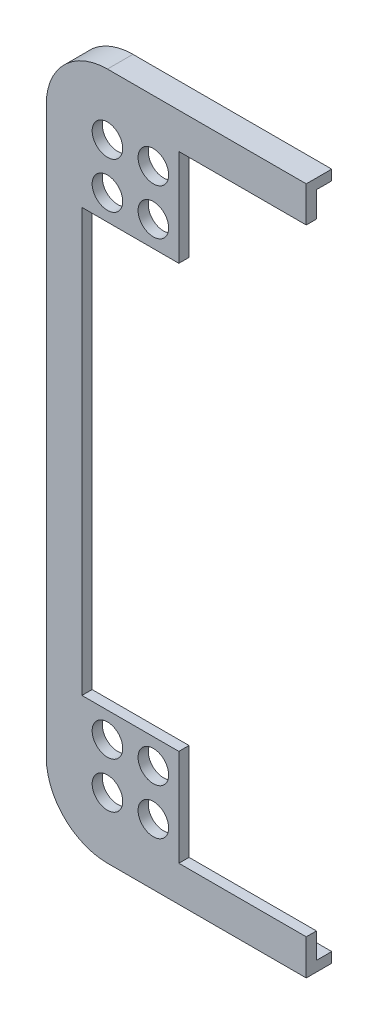
SolidWorks part; units mm, degrees
ref_plane "Front Plane" through (0, 0, 0) normal (0, 0, 1) x (1, 0, 0)
ref_plane "Top Plane" through (0, 0, 0) normal (0, 1, 0) x (1, 0, 0)
ref_plane "Right Plane" through (0, 0, 0) normal (1, 0, 0) x (0, 0, -1)
sketch "Sketch1" plane through (0, 0, 0) normal (0, 0, 1) x (1, 0, 0)
  line L0 (157.8919, 26.2701) -> (191.7747, 29.0915)
  line L1 (157.8919, 26.2701) -> (191.7747, 26.2701)
  line L2 (157.8919, 26.2701) -> (157.8919, 29.0915)
  line L3 (157.8919, 29.0915) -> (191.7747, 29.0915)
  line L4 (191.7747, 26.2701) -> (191.7747, 29.0915)
  line L5 (123.8919, 26.2701) -> (90.0092, 26.2701)
  line L6 (123.8919, 26.2701) -> (123.8919, 29.0915)
  line L7 (123.8919, 29.0915) -> (90.0092, 29.0915)
  line L8 (90.0092, 26.2701) -> (90.0092, 29.0915)
  line L9 (90.0092, 29.0915) -> (123.8919, 26.2701)
  line L10 (168.0919, 58.3601) -> (194.8735, 70.7292)
  line L11 (168.0919, 58.3601) -> (194.8735, 58.3601)
  line L12 (168.0919, 58.3601) -> (168.0919, 70.7292)
  line L13 (168.0919, 70.7292) -> (194.8735, 70.7292)
  line L14 (194.8735, 58.3601) -> (194.8735, 70.7292)
  line L15 (194.8735, 70.7292) -> (224.3587, 70.7292)
  line L16 (194.8735, 70.7292) -> (194.8735, 69.7923)
  line L17 (194.8735, 69.7923) -> (224.3587, 69.7923)
  line L18 (224.3587, 70.7292) -> (224.3587, 69.7923)
  line L19 (224.3587, 69.7923) -> (253.5106, 69.7923)
  line L20 (224.3587, 69.7923) -> (224.3587, 65.2742)
  line L21 (224.3587, 65.2742) -> (253.5106, 65.2742)
  line L22 (253.5106, 69.7923) -> (253.5106, 65.2742)
  line L23 (224.3587, 69.7923) -> (194.8735, 70.7292)
  line L24 (253.5106, 65.2742) -> (224.3587, 69.7923)
  line L25 (170.7502, 87.7401) -> (168.0919, 58.3601)
  line L26 (168.0919, 58.3601) -> (170.7502, 58.3601)
  line L27 (168.0919, 58.3601) -> (168.0919, 87.7401)
  line L28 (168.0919, 87.7401) -> (170.7502, 87.7401)
  line L29 (170.7502, 58.3601) -> (170.7502, 87.7401)
  line L30 (52.9966, 89.4705) -> (24.4119, 82.1791)
  line L31 (24.4119, 82.1791) -> (52.9966, 82.1791)
  line L32 (24.4119, 82.1791) -> (24.4119, 89.4705)
  line L33 (24.4119, 89.4705) -> (52.9966, 89.4705)
  line L34 (52.9966, 82.1791) -> (52.9966, 89.4705)
  line L35 (82.4966, 89.4705) -> (109.0019, 89.4705)
  line L36 (82.4966, 89.4705) -> (82.4966, 76.5201)
  line L37 (82.4966, 76.5201) -> (109.0019, 76.5201)
  line L38 (109.0019, 89.4705) -> (109.0019, 76.5201)
  line L39 (92.4554, 117.2387) -> (82.4966, 117.2387)
  line L40 (92.4554, 117.2387) -> (92.4554, 89.4705)
  line L41 (92.4554, 89.4705) -> (82.4966, 89.4705)
  line L42 (82.4966, 117.2387) -> (82.4966, 89.4705)
  line L43 (92.4554, 117.2387) -> (82.4966, 89.4705)
  line L44 (109.0019, 76.5201) -> (82.4966, 89.4705)
  circle A0 centre (123.8919, 26.2701) radius 14.25
  circle A1 centre (157.8919, 26.2701) radius 14.25
  circle A2 centre (90.0092, 29.0915) radius 14.25
  circle A3 centre (191.7747, 29.0915) radius 14.25
  circle A4 centre (82.4966, 89.4705) radius 11.25
  circle A5 centre (92.4554, 117.2387) radius 11.25
  circle A6 centre (52.9966, 89.4705) radius 11.25
  circle A7 centre (109.0019, 76.5201) radius 11.25
  circle A8 centre (24.4119, 82.1791) radius 11.25
  circle A9 centre (170.7502, 87.7401) radius 11.25
  circle A10 centre (168.0919, 58.3601) radius 11.25
  circle A11 centre (197.5318, 100.1092) radius 11.25
  circle A12 centre (194.8735, 70.7292) radius 11.25
  circle A13 centre (227.0169, 99.1723) radius 11.25
  circle A14 centre (224.3587, 69.7923) radius 11.25
  circle A15 centre (256.1689, 94.6541) radius 11.25
  circle A16 centre (253.5106, 65.2742) radius 11.25
  circle A17 centre (24.4119, 82.1791) radius 12
  circle A18 centre (52.9966, 89.4705) radius 12
  circle A19 centre (92.4554, 117.2387) radius 12
  circle A20 centre (82.4966, 89.4705) radius 12
  circle A21 centre (109.0019, 76.5201) radius 12
  circle A22 centre (168.0919, 58.3601) radius 12
  circle A23 centre (194.8735, 70.7292) radius 12
  circle A24 centre (224.3587, 69.7923) radius 12
  circle A25 centre (253.5106, 65.2742) radius 12
  circle A26 centre (256.1689, 94.6541) radius 12
  circle A27 centre (227.0169, 99.1723) radius 12
  circle A28 centre (197.5318, 100.1092) radius 12
  circle A29 centre (170.7502, 87.7401) radius 12
  circle A30 centre (191.7747, 29.0915) radius 15
  circle A31 centre (157.8919, 26.2701) radius 15
  circle A32 centre (123.8919, 26.2701) radius 15
  circle A33 centre (90.0092, 29.0915) radius 15
  circle A34 centre (173.429, 117.1182) radius 11.25
  circle A35 centre (173.429, 117.1182) radius 12
  dimension "D1" = 28.5
  dimension "D2" = 22.5
  dimension "D3" = 0.75
  dimension "D4" = 0.75
  dimension "D34" = 34
  dimension "D5" = 29.5
  dimension "D6" = 29.5
  dimension "D7" = 29.5
  dimension "D8" = 29.5
  dimension "D9" = 29.5
  dimension "D10" = 29.5
  dimension "D11" = 29.5
  dimension "D12" = 29.5
  dimension "D13" = 29.5
  dimension "D14" = 29.5
  dimension "D15" = 29.5
  dimension "D16" = 29.5
  dimension "D17" = 29.5
  dimension "D18" = 29.5
  dimension "D19" = 34
  dimension "D20" = 34
  dimension "D21" = 32.09
  dimension "D22" = 10.2
  dimension "D23" = 4.76
  dimension "D24" = 4.76
  dimension "D25" = 24.79
  dimension "D26" = 1.82
  dimension "D27" = 8.81
  dimension "D28" = 84.83
  dimension "D29" = 75.69
  dimension "D30" = 70.27
  dimension "D31" = 26.04
  dimension "D32" = 14.89
  dimension "D33" = 50.25
  dimension "D35" = 29.5
  dimension "D36" = 29.5
sketch "Sketch4" plane through (-30.2083, 20.075, 0) normal (0, 0, 1) x (0.9781, -0.2079, 0)
  line L0 (86.1706, 94.1917) -> (105.2206, 75.1417)
  line L1 (67.1206, 94.1917) -> (86.1706, 94.1917)
  line L2 (67.1206, 94.1917) -> (67.1206, 75.1417)
  line L3 (67.1206, 75.1417) -> (86.1706, 75.1417)
  line L4 (86.1706, 94.1917) -> (86.1706, 75.1417)
  line L5 (86.1706, 94.1917) -> (105.2206, 94.1917)
  line L6 (86.1706, 94.1917) -> (86.1706, 75.1417)
  line L7 (86.1706, 75.1417) -> (105.2206, 75.1417)
  line L8 (105.2206, 94.1917) -> (105.2206, 75.1417)
  line L9 (105.2206, 94.1917) -> (124.2706, 94.1917)
  line L10 (105.2206, 94.1917) -> (105.2206, 75.1417)
  line L11 (105.2206, 75.1417) -> (124.2706, 75.1417)
  line L12 (124.2706, 94.1917) -> (124.2706, 75.1417)
  line L13 (86.1706, 94.1917) -> (105.2206, 94.1917)
  line L14 (86.1706, 94.1917) -> (86.1706, 113.2417)
  line L15 (86.1706, 113.2417) -> (105.2206, 113.2417)
  line L16 (105.2206, 94.1917) -> (105.2206, 113.2417)
  line L17 (66.9585, 85.1784) -> (124.4326, 84.1551)
  point P14 (95.6956, 84.6667)
  point P15 (95.6956, 84.6667)
  dimension "D1" = 19.05
sketch "Sketch9" plane through (0, 0, 0) normal (0, 0, 1) x (1, 0, 0)
  line L1 (17.3619, 89.2291) -> (31.4619, 89.2291)
  line L2 (17.3619, 89.2291) -> (17.3619, 75.1291)
  line L3 (17.3619, 75.1291) -> (31.4619, 75.1291)
  line L4 (31.4619, 89.2291) -> (31.4619, 75.1291)
  line L5 (45.9466, 96.5205) -> (60.0466, 96.5205)
  line L6 (45.9466, 96.5205) -> (45.9466, 82.4205)
  line L7 (45.9466, 82.4205) -> (60.0466, 82.4205)
  line L8 (60.0466, 96.5205) -> (60.0466, 82.4205)
  line L9 (75.4466, 96.5205) -> (89.5466, 96.5205)
  line L10 (75.4466, 96.5205) -> (75.4466, 82.4205)
  line L11 (75.4466, 82.4205) -> (89.5466, 82.4205)
  line L12 (89.5466, 96.5205) -> (89.5466, 82.4205)
  line L13 (101.9519, 83.5701) -> (116.0519, 83.5701)
  line L14 (101.9519, 83.5701) -> (101.9519, 69.4701)
  line L15 (101.9519, 69.4701) -> (116.0519, 69.4701)
  line L16 (116.0519, 83.5701) -> (116.0519, 69.4701)
  line L17 (85.4054, 124.2887) -> (99.5054, 124.2887)
  line L18 (85.4054, 124.2887) -> (85.4054, 110.1887)
  line L19 (85.4054, 110.1887) -> (99.5054, 110.1887)
  line L20 (99.5054, 124.2887) -> (99.5054, 110.1887)
  line L21 (82.9592, 36.1415) -> (97.0592, 36.1415)
  line L22 (82.9592, 36.1415) -> (82.9592, 22.0415)
  line L23 (82.9592, 22.0415) -> (97.0592, 22.0415)
  line L24 (97.0592, 36.1415) -> (97.0592, 22.0415)
  line L25 (116.8419, 33.3201) -> (130.9419, 33.3201)
  line L26 (116.8419, 33.3201) -> (116.8419, 19.2201)
  line L27 (116.8419, 19.2201) -> (130.9419, 19.2201)
  line L28 (130.9419, 33.3201) -> (130.9419, 19.2201)
  line L29 (150.8419, 33.3201) -> (164.9419, 33.3201)
  line L30 (150.8419, 33.3201) -> (150.8419, 19.2201)
  line L31 (150.8419, 19.2201) -> (164.9419, 19.2201)
  line L32 (164.9419, 33.3201) -> (164.9419, 19.2201)
  line L33 (184.7247, 36.1415) -> (198.8247, 36.1415)
  line L34 (184.7247, 36.1415) -> (184.7247, 22.0415)
  line L35 (184.7247, 22.0415) -> (198.8247, 22.0415)
  line L36 (198.8247, 36.1415) -> (198.8247, 22.0415)
  line L37 (260.5606, 58.2242) -> (246.4606, 58.2242)
  line L38 (260.5606, 58.2242) -> (260.5606, 72.3242)
  line L39 (260.5606, 72.3242) -> (246.4606, 72.3242)
  line L40 (246.4606, 58.2242) -> (246.4606, 72.3242)
  line L41 (217.3087, 76.8423) -> (231.4087, 76.8423)
  line L42 (217.3087, 76.8423) -> (217.3087, 62.7423)
  line L43 (217.3087, 62.7423) -> (231.4087, 62.7423)
  line L44 (231.4087, 76.8423) -> (231.4087, 62.7423)
  line L45 (187.8235, 77.7792) -> (201.9235, 77.7792)
  line L46 (187.8235, 77.7792) -> (187.8235, 63.6792)
  line L47 (187.8235, 63.6792) -> (201.9235, 63.6792)
  line L48 (201.9235, 77.7792) -> (201.9235, 63.6792)
  line L49 (161.0419, 65.4101) -> (175.1419, 65.4101)
  line L50 (161.0419, 65.4101) -> (161.0419, 51.3101)
  line L51 (161.0419, 51.3101) -> (175.1419, 51.3101)
  line L52 (175.1419, 65.4101) -> (175.1419, 51.3101)
  line L53 (163.7002, 94.7901) -> (177.8002, 94.7901)
  line L54 (163.7002, 94.7901) -> (163.7002, 80.6901)
  line L55 (163.7002, 80.6901) -> (177.8002, 80.6901)
  line L56 (177.8002, 94.7901) -> (177.8002, 80.6901)
  line L57 (190.4818, 107.1592) -> (204.5818, 107.1592)
  line L58 (190.4818, 107.1592) -> (190.4818, 93.0592)
  line L59 (190.4818, 93.0592) -> (204.5818, 93.0592)
  line L60 (204.5818, 107.1592) -> (204.5818, 93.0592)
  line L61 (219.9669, 106.2223) -> (234.0669, 106.2223)
  line L62 (219.9669, 106.2223) -> (219.9669, 92.1223)
  line L63 (219.9669, 92.1223) -> (234.0669, 92.1223)
  line L64 (234.0669, 106.2223) -> (234.0669, 92.1223)
  line L65 (249.1189, 101.7041) -> (263.2189, 101.7041)
  line L66 (249.1189, 101.7041) -> (249.1189, 87.6041)
  line L67 (249.1189, 87.6041) -> (263.2189, 87.6041)
  line L68 (263.2189, 101.7041) -> (263.2189, 87.6041)
  line L69 (166.379, 124.1682) -> (180.479, 124.1682)
  line L70 (166.379, 124.1682) -> (166.379, 110.0682)
  line L71 (166.379, 110.0682) -> (180.479, 110.0682)
  line L72 (180.479, 124.1682) -> (180.479, 110.0682)
  point P72 (24.4119, 89.2291)
  point P74 (52.9966, 96.5205)
  point P76 (82.4966, 96.5205)
  point P78 (92.4554, 124.2887)
  point P80 (109.0019, 83.5701)
  point P82 (90.0092, 36.1415)
  point P84 (123.8919, 33.3201)
  point P86 (157.8919, 33.3201)
  point P88 (191.7747, 36.1415)
  point P90 (168.0919, 65.4101)
  point P92 (170.7502, 94.7901)
  point P94 (173.429, 124.1682)
  point P96 (197.5318, 107.1592)
  point P98 (227.0169, 106.2223)
  point P100 (256.1689, 101.7041)
  point P102 (194.8735, 77.7792)
  point P104 (224.3587, 76.8423)
  point P106 (253.5106, 72.3242)
  point P108 (17.3619, 82.1791)
  point P109 (45.9466, 89.4705)
  point P110 (75.4466, 89.4705)
  point P111 (101.9519, 76.5201)
  point P112 (85.4054, 117.2387)
  point P113 (82.9592, 29.0915)
  point P114 (116.8419, 26.2701)
  point P115 (150.8419, 26.2701)
  point P116 (184.7247, 29.0915)
  point P118 (161.0419, 58.3601)
  point P119 (187.8235, 70.7292)
  point P120 (217.3087, 69.7923)
  point P121 (246.4606, 65.2742)
  point P122 (163.7002, 87.7401)
  point P123 (190.4818, 100.1092)
  point P124 (219.9669, 99.1723)
  point P125 (249.1189, 94.6541)
  point P126 (166.379, 117.1182)
  dimension "D1" = 14.1
sketch "Sketch10" plane through (-22.0981, 19.3454, 0) normal (0, 0, 1) x (0.9781, -0.2079, 0)
  line L1 (61.5108, 90.7441) -> (75.6108, 90.7441)
  line L2 (61.5108, 90.7441) -> (61.5108, 76.6441)
  line L3 (61.5108, 76.6441) -> (75.6108, 76.6441)
  line L4 (75.6108, 90.7441) -> (75.6108, 76.6441)
  line L5 (80.5608, 90.7441) -> (94.6608, 90.7441)
  line L6 (80.5608, 90.7441) -> (80.5608, 76.6441)
  line L7 (80.5608, 76.6441) -> (94.6608, 76.6441)
  line L8 (94.6608, 90.7441) -> (94.6608, 76.6441)
  line L9 (99.6108, 90.7441) -> (113.7108, 90.7441)
  line L10 (99.6108, 90.7441) -> (99.6108, 76.6441)
  line L11 (99.6108, 76.6441) -> (113.7108, 76.6441)
  line L12 (113.7108, 90.7441) -> (113.7108, 76.6441)
  line L13 (80.5608, 109.7941) -> (94.6608, 109.7941)
  line L14 (80.5608, 109.7941) -> (80.5608, 95.6941)
  line L15 (80.5608, 95.6941) -> (94.6608, 95.6941)
  line L16 (94.6608, 109.7941) -> (94.6608, 95.6941)
  line L17 (50.5121, 89.6359) -> (53.4436, 75.8441) construction
  line L18 (59.0358, 93.2191) -> (78.0858, 93.2191) construction
  line L19 (78.0858, 112.2691) -> (97.1358, 112.2691) construction
  line L20 (97.1358, 93.2191) -> (116.1858, 93.2191) construction
  line L21 (78.0858, 93.2191) -> (78.0858, 112.2691) construction
  line L23 (59.0358, 93.2191) -> (59.0358, 74.1691) construction
  point P16 (75.6108, 83.6941)
  point P17 (94.6608, 83.6941)
  point P18 (113.7108, 83.6941)
  point P19 (87.6108, 90.7441)
  point P20 (87.6108, 109.7941)
  point P23 (68.5608, 90.7441)
  point P26 (68.5608, 93.2191)
  point P29 (87.6108, 112.2691)
  point P30 (106.6608, 90.7441)
  point P33 (106.6608, 93.2191)
  point P34 (80.5608, 102.7441)
  point P37 (78.0858, 102.7441)
  point P42 (59.0358, 83.6941)
  point P43 (61.5108, 83.6941)
sketch "Sketch14" plane through (0, 0, 0) normal (0, 0, 1) x (1, 0, 0)
  line L0 (165.1144, 80.6901) -> (163.7002, 82.1043)
  line L1 (163.7002, 93.3758) -> (165.1144, 94.7901)
  line L2 (177.8002, 93.3758) -> (176.386, 94.7901)
  line L3 (179.0648, 110.0682) -> (180.479, 111.4824)
  line L4 (166.379, 111.4824) -> (167.7932, 110.0682)
  line L5 (166.379, 122.754) -> (167.7932, 124.1682)
  line L6 (179.0648, 124.1682) -> (180.479, 122.754)
  line L7 (203.1676, 93.0592) -> (204.5818, 94.4734)
  line L8 (17.3619, 89.2291) -> (17.3619, 75.1291) construction
  line L9 (17.3619, 89.2291) -> (31.4619, 89.2291) construction
  line L10 (17.3619, 87.8149) -> (18.7761, 89.2291)
  line L11 (17.3619, 75.1291) -> (31.4619, 75.1291) construction
  line L12 (31.4619, 89.2291) -> (31.4619, 75.1291) construction
  line L13 (45.9466, 96.5205) -> (60.0466, 96.5205) construction
  line L14 (60.0466, 96.5205) -> (60.0466, 82.4205) construction
  line L15 (45.9466, 96.5205) -> (45.9466, 82.4205) construction
  line L16 (45.9466, 82.4205) -> (60.0466, 82.4205) construction
  line L17 (85.4054, 124.2887) -> (85.4054, 110.1887) construction
  line L18 (85.4054, 124.2887) -> (99.5054, 124.2887) construction
  line L19 (99.5054, 124.2887) -> (99.5054, 110.1887) construction
  line L20 (85.4054, 110.1887) -> (99.5054, 110.1887) construction
  line L21 (101.9519, 83.5701) -> (101.9519, 69.4701) construction
  line L22 (101.9519, 83.5701) -> (116.0519, 83.5701) construction
  line L23 (116.0519, 83.5701) -> (116.0519, 69.4701) construction
  line L24 (101.9519, 69.4701) -> (116.0519, 69.4701) construction
  line L25 (91.2712, 73.6044) -> (105.0631, 70.6729) construction
  line L26 (107.9947, 84.4647) -> (105.0631, 70.6729) construction
  line L27 (94.2028, 87.3963) -> (107.9947, 84.4647) construction
  line L28 (94.2028, 87.3963) -> (91.2712, 73.6044) construction
  line L29 (72.6375, 77.5651) -> (86.4294, 74.6336) construction
  line L30 (89.361, 88.4255) -> (86.4294, 74.6336) construction
  line L31 (75.5691, 91.357) -> (89.361, 88.4255) construction
  line L32 (75.5691, 91.357) -> (72.6375, 77.5651) construction
  line L33 (56.9354, 95.3177) -> (54.0038, 81.5259) construction
  line L34 (56.9354, 95.3177) -> (70.7273, 92.3862) construction
  line L35 (70.7273, 92.3862) -> (67.7957, 78.5943) construction
  line L36 (54.0038, 81.5259) -> (67.7957, 78.5943) construction
  line L37 (76.5983, 96.1988) -> (90.3901, 93.2673) construction
  line L38 (93.3217, 107.0592) -> (90.3901, 93.2673) construction
  line L39 (79.5298, 109.9907) -> (76.5983, 96.1988) construction
  line L40 (79.5298, 109.9907) -> (93.3217, 107.0592) construction
  line L41 (82.9592, 36.1415) -> (82.9592, 22.0415) construction
  line L42 (82.9592, 36.1415) -> (97.0592, 36.1415) construction
  line L43 (82.9592, 22.0415) -> (97.0592, 22.0415) construction
  line L44 (97.0592, 36.1415) -> (97.0592, 22.0415) construction
  line L45 (116.8419, 33.3201) -> (116.8419, 19.2201) construction
  line L46 (116.8419, 33.3201) -> (130.9419, 33.3201) construction
  line L47 (116.8419, 19.2201) -> (130.9419, 19.2201) construction
  line L48 (130.9419, 33.3201) -> (130.9419, 19.2201) construction
  line L49 (150.8419, 33.3201) -> (150.8419, 19.2201) construction
  line L50 (150.8419, 33.3201) -> (164.9419, 33.3201) construction
  line L51 (164.9419, 33.3201) -> (164.9419, 19.2201) construction
  line L52 (150.8419, 19.2201) -> (164.9419, 19.2201) construction
  line L53 (184.7247, 36.1415) -> (184.7247, 22.0415) construction
  line L54 (184.7247, 22.0415) -> (198.8247, 22.0415) construction
  line L55 (198.8247, 36.1415) -> (198.8247, 22.0415) construction
  line L56 (184.7247, 36.1415) -> (198.8247, 36.1415) construction
  line L57 (161.0419, 65.4101) -> (175.1419, 65.4101) construction
  line L58 (175.1419, 65.4101) -> (175.1419, 51.3101) construction
  line L59 (161.0419, 51.3101) -> (175.1419, 51.3101) construction
  line L60 (161.0419, 65.4101) -> (161.0419, 51.3101) construction
  line L61 (187.8235, 77.7792) -> (187.8235, 63.6792) construction
  line L62 (187.8235, 77.7792) -> (201.9235, 77.7792) construction
  line L63 (187.8235, 63.6792) -> (201.9235, 63.6792) construction
  line L64 (201.9235, 77.7792) -> (201.9235, 63.6792) construction
  line L65 (217.3087, 76.8423) -> (217.3087, 62.7423) construction
  line L66 (217.3087, 76.8423) -> (231.4087, 76.8423) construction
  line L67 (231.4087, 76.8423) -> (231.4087, 62.7423) construction
  line L68 (217.3087, 62.7423) -> (231.4087, 62.7423) construction
  line L69 (260.5606, 58.2242) -> (246.4606, 58.2242) construction
  line L70 (260.5606, 58.2242) -> (260.5606, 72.3242) construction
  line L71 (246.4606, 58.2242) -> (246.4606, 72.3242) construction
  line L72 (260.5606, 72.3242) -> (246.4606, 72.3242) construction
  line L73 (249.1189, 101.7041) -> (263.2189, 101.7041) construction
  line L74 (263.2189, 101.7041) -> (263.2189, 87.6041) construction
  line L75 (249.1189, 87.6041) -> (263.2189, 87.6041) construction
  line L76 (249.1189, 101.7041) -> (249.1189, 87.6041) construction
  line L77 (219.9669, 106.2223) -> (219.9669, 92.1223) construction
  line L78 (219.9669, 106.2223) -> (234.0669, 106.2223) construction
  line L79 (234.0669, 106.2223) -> (234.0669, 92.1223) construction
  line L80 (219.9669, 92.1223) -> (234.0669, 92.1223) construction
  line L81 (190.4818, 107.1592) -> (204.5818, 107.1592) construction
  line L82 (204.5818, 107.1592) -> (204.5818, 93.0592) construction
  line L83 (190.4818, 93.0592) -> (204.5818, 93.0592) construction
  line L84 (190.4818, 107.1592) -> (190.4818, 93.0592) construction
  line L85 (163.7002, 94.7901) -> (177.8002, 94.7901) construction
  line L86 (177.8002, 94.7901) -> (177.8002, 80.6901) construction
  line L87 (163.7002, 80.6901) -> (177.8002, 80.6901) construction
  line L88 (163.7002, 94.7901) -> (163.7002, 80.6901) construction
  line L89 (180.479, 124.1682) -> (180.479, 110.0682) construction
  line L90 (166.379, 110.0682) -> (180.479, 110.0682) construction
  line L91 (166.379, 124.1682) -> (166.379, 110.0682) construction
  line L92 (166.379, 124.1682) -> (180.479, 124.1682) construction
  line L93 (17.3619, 76.5433) -> (18.7761, 75.1291)
  line L94 (30.0477, 75.1291) -> (31.4619, 76.5433)
  line L95 (31.4619, 87.8149) -> (30.0477, 89.2291)
  line L96 (45.9466, 95.1063) -> (47.3608, 96.5205)
  line L97 (45.9466, 83.8347) -> (47.3608, 82.4205)
  line L98 (54.2979, 82.9092) -> (55.3871, 81.2318)
  line L99 (58.6323, 82.4205) -> (60.0466, 83.8347)
  line L100 (56.6413, 93.9344) -> (58.3187, 95.0237)
  line L101 (58.6323, 96.5205) -> (60.0466, 95.1063)
  line L102 (69.3439, 92.6802) -> (70.4332, 91.0029)
  line L103 (68.0897, 79.9776) -> (66.4124, 78.8883)
  line L104 (75.2751, 89.9737) -> (76.9524, 91.063)
  line L105 (72.9316, 78.9484) -> (74.0208, 77.2711)
  line L106 (85.0461, 74.9276) -> (86.7234, 76.0169)
  line L107 (89.0669, 87.0421) -> (87.9777, 88.7195)
  line L108 (89.0068, 93.5613) -> (90.6842, 94.6506)
  line L109 (76.8923, 97.5822) -> (77.9816, 95.9048)
  line L110 (91.9384, 107.3532) -> (93.0277, 105.6759)
  line L111 (79.2358, 108.6074) -> (80.9131, 109.6967)
  line L112 (85.4054, 111.6029) -> (86.8196, 110.1887)
  line L113 (98.0912, 110.1887) -> (99.5054, 111.6029)
  line L114 (98.0912, 124.2887) -> (99.5054, 122.8745)
  line L115 (85.4054, 122.8745) -> (86.8196, 124.2887)
  line L116 (93.9088, 86.013) -> (95.5861, 87.1023)
  line L117 (91.5653, 74.9877) -> (92.6546, 73.3104)
  line L118 (103.6798, 70.9669) -> (105.3572, 72.0562)
  line L119 (106.6114, 84.7588) -> (107.7006, 83.0814)
  line L120 (101.9519, 82.1559) -> (103.3662, 83.5701)
  line L121 (101.9519, 70.8843) -> (103.3662, 69.4701)
  line L122 (114.6377, 69.4701) -> (116.0519, 70.8843)
  line L123 (116.0519, 82.1559) -> (114.6377, 83.5701)
  line L124 (82.9592, 34.7272) -> (84.3734, 36.1415)
  line L125 (82.9592, 23.4557) -> (84.3734, 22.0415)
  line L126 (95.645, 22.0415) -> (97.0592, 23.4557)
  line L127 (97.0592, 34.7272) -> (95.645, 36.1415)
  line L128 (116.8419, 31.9059) -> (118.2562, 33.3201)
  line L129 (116.8419, 20.6343) -> (118.2562, 19.2201)
  line L130 (129.5277, 19.2201) -> (130.9419, 20.6343)
  line L131 (130.9419, 31.9059) -> (129.5277, 33.3201)
  line L132 (150.8419, 31.9059) -> (152.2562, 33.3201)
  line L133 (150.8419, 20.6343) -> (152.2562, 19.2201)
  line L134 (163.5277, 19.2201) -> (164.9419, 20.6343)
  line L135 (164.9419, 31.9059) -> (163.5277, 33.3201)
  line L136 (184.7247, 34.7272) -> (186.1389, 36.1415)
  line L137 (184.7247, 23.4557) -> (186.1389, 22.0415)
  line L138 (197.4105, 22.0415) -> (198.8247, 23.4557)
  line L139 (198.8247, 34.7272) -> (197.4105, 36.1415)
  line L140 (173.7277, 51.3101) -> (175.1419, 52.7243)
  line L141 (161.0419, 52.7243) -> (162.4562, 51.3101)
  line L142 (161.0419, 63.9959) -> (162.4562, 65.4101)
  line L143 (173.7277, 65.4101) -> (175.1419, 63.9959)
  line L144 (187.8235, 65.0934) -> (189.2378, 63.6792)
  line L145 (200.5093, 63.6792) -> (201.9235, 65.0934)
  line L146 (200.5093, 77.7792) -> (201.9235, 76.365)
  line L147 (187.8235, 76.365) -> (189.2378, 77.7792)
  line L148 (176.386, 80.6901) -> (177.8002, 82.1043)
  line L149 (204.5818, 105.745) -> (203.1676, 107.1592)
  line L150 (191.896, 107.1592) -> (190.4818, 105.745)
  line L151 (190.4818, 94.4734) -> (191.896, 93.0592)
  line L152 (219.9669, 104.8081) -> (221.3812, 106.2223)
  line L153 (232.6527, 106.2223) -> (234.0669, 104.8081)
  line L154 (234.0669, 93.5365) -> (232.6527, 92.1223)
  line L155 (219.9669, 93.5365) -> (221.3812, 92.1223)
  line L156 (229.9944, 76.8423) -> (231.4087, 75.4281)
  line L157 (217.3087, 75.4281) -> (218.7229, 76.8423)
  line L158 (217.3087, 64.1565) -> (218.7229, 62.7423)
  line L159 (229.9944, 62.7423) -> (231.4087, 64.1565)
  line L160 (259.1464, 72.3242) -> (260.5606, 70.9099)
  line L161 (246.4606, 70.9099) -> (247.8748, 72.3242)
  line L162 (259.1464, 58.2242) -> (260.5606, 59.6384)
  line L163 (247.8748, 58.2242) -> (246.4606, 59.6384)
  line L164 (261.8047, 87.6041) -> (263.2189, 89.0183)
  line L165 (249.1189, 89.0183) -> (250.5331, 87.6041)
  line L166 (249.1189, 100.2899) -> (250.5331, 101.7041)
  line L167 (261.8047, 101.7041) -> (263.2189, 100.2899)
  line L168 (75.4466, 96.5205) -> (75.4466, 82.4205) construction
  line L169 (75.4466, 96.5205) -> (89.5466, 96.5205) construction
  line L170 (89.5466, 96.5205) -> (89.5466, 82.4205) construction
  line L171 (75.4466, 82.4205) -> (89.5466, 82.4205) construction
  line L172 (76.8608, 96.5205) -> (75.4466, 95.1063)
  line L173 (88.1323, 96.5205) -> (89.5466, 95.1063)
  line L174 (89.5466, 83.8347) -> (88.1323, 82.4205)
  line L175 (75.4466, 83.8347) -> (76.8608, 82.4205)
  arc A0 (17.3619, 87.8149) -> (18.7761, 89.2291) centre (18.069, 88.522) cw
  arc A1 (18.7761, 75.1291) -> (17.3619, 76.5433) centre (18.069, 75.8362) cw
  arc A2 (31.4619, 76.5433) -> (30.0477, 75.1291) centre (30.7548, 75.8362) cw
  arc A3 (30.0477, 89.2291) -> (31.4619, 87.8149) centre (30.7548, 88.522) cw
  arc A4 (58.6323, 96.5205) -> (60.0466, 95.1063) centre (59.3394, 95.8134) cw
  arc A5 (45.9466, 95.1063) -> (47.3608, 96.5205) centre (46.6537, 95.8134) cw
  arc A6 (47.3608, 82.4205) -> (45.9466, 83.8347) centre (46.6537, 83.1276) cw
  arc A7 (60.0466, 83.8347) -> (58.6323, 82.4205) centre (59.3394, 83.1276) cw
  arc A8 (85.4054, 122.8745) -> (86.8196, 124.2887) centre (86.1125, 123.5816) cw
  arc A9 (98.0912, 124.2887) -> (99.5054, 122.8745) centre (98.7983, 123.5816) cw
  arc A10 (99.5054, 111.6029) -> (98.0912, 110.1887) centre (98.7983, 110.8958) cw
  arc A11 (85.4054, 111.6029) -> (86.8196, 110.1887) centre (86.1125, 110.8958) ccw
  arc A12 (101.9519, 82.1559) -> (103.3662, 83.5701) centre (102.6591, 82.863) cw
  arc A13 (114.6377, 83.5701) -> (116.0519, 82.1559) centre (115.3448, 82.863) cw
  arc A14 (116.0519, 70.8843) -> (114.6377, 69.4701) centre (115.3448, 70.1772) cw
  arc A15 (101.9519, 70.8843) -> (103.3662, 69.4701) centre (102.6591, 70.1772) ccw
  arc A16 (103.6798, 70.9669) -> (105.3572, 72.0562) centre (104.5185, 71.5115) ccw
  arc A17 (106.6114, 84.7588) -> (107.7006, 83.0814) centre (107.156, 83.9201) cw
  arc A18 (93.9088, 86.013) -> (95.5861, 87.1023) centre (94.7474, 86.5576) cw
  arc A19 (91.5653, 74.9877) -> (92.6546, 73.3104) centre (92.1099, 74.1491) ccw
  arc A20 (85.0461, 74.9276) -> (86.7234, 76.0169) centre (85.8848, 75.4722) ccw
  arc A21 (87.9777, 88.7195) -> (89.0669, 87.0421) centre (88.5223, 87.8808) cw
  arc A22 (75.2751, 89.9737) -> (76.9524, 91.063) centre (76.1137, 90.5183) cw
  arc A23 (72.9316, 78.9484) -> (74.0208, 77.2711) centre (73.4762, 78.1098) ccw
  arc A24 (56.6413, 93.9344) -> (58.3187, 95.0237) centre (57.48, 94.4791) cw
  arc A25 (69.3439, 92.6802) -> (70.4332, 91.0029) centre (69.8886, 91.8415) cw
  arc A26 (68.0897, 79.9776) -> (66.4124, 78.8883) centre (67.2511, 79.433) cw
  arc A27 (54.2979, 82.9092) -> (55.3871, 81.2318) centre (54.8425, 82.0705) ccw
  arc A28 (89.0068, 93.5613) -> (90.6842, 94.6506) centre (89.8455, 94.106) ccw
  arc A29 (76.8923, 97.5822) -> (77.9816, 95.9048) centre (77.4369, 96.7435) ccw
  arc A30 (79.2358, 108.6074) -> (80.9131, 109.6967) centre (80.0744, 109.1521) cw
  arc A31 (91.9384, 107.3532) -> (93.0277, 105.6759) centre (92.483, 106.5145) cw
  arc A32 (82.9592, 34.7272) -> (84.3734, 36.1415) centre (83.6663, 35.4344) cw
  arc A33 (82.9592, 23.4557) -> (84.3734, 22.0415) centre (83.6663, 22.7486) ccw
  arc A34 (95.645, 22.0415) -> (97.0592, 23.4557) centre (96.3521, 22.7486) ccw
  arc A35 (95.645, 36.1415) -> (97.0592, 34.7272) centre (96.3521, 35.4344) cw
  arc A36 (116.8419, 31.9059) -> (118.2562, 33.3201) centre (117.5491, 32.613) cw
  arc A37 (116.8419, 20.6343) -> (118.2562, 19.2201) centre (117.5491, 19.9272) ccw
  arc A38 (129.5277, 19.2201) -> (130.9419, 20.6343) centre (130.2348, 19.9272) ccw
  arc A39 (129.5277, 33.3201) -> (130.9419, 31.9059) centre (130.2348, 32.613) cw
  arc A40 (150.8419, 31.9059) -> (152.2562, 33.3201) centre (151.5491, 32.613) cw
  arc A41 (163.5277, 33.3201) -> (164.9419, 31.9059) centre (164.2348, 32.613) cw
  arc A42 (164.9419, 20.6343) -> (163.5277, 19.2201) centre (164.2348, 19.9272) cw
  arc A43 (150.8419, 20.6343) -> (152.2562, 19.2201) centre (151.5491, 19.9272) ccw
  arc A44 (184.7247, 23.4557) -> (186.1389, 22.0415) centre (185.4318, 22.7486) ccw
  arc A45 (197.4105, 22.0415) -> (198.8247, 23.4557) centre (198.1176, 22.7486) ccw
  arc A46 (197.4105, 36.1415) -> (198.8247, 34.7272) centre (198.1176, 35.4344) cw
  arc A47 (184.7247, 34.7272) -> (186.1389, 36.1415) centre (185.4318, 35.4344) cw
  arc A48 (173.7277, 65.4101) -> (175.1419, 63.9959) centre (174.4348, 64.703) cw
  arc A49 (175.1419, 52.7243) -> (173.7277, 51.3101) centre (174.4348, 52.0172) cw
  arc A50 (161.0419, 52.7243) -> (162.4562, 51.3101) centre (161.7491, 52.0172) ccw
  arc A51 (161.0419, 63.9959) -> (162.4562, 65.4101) centre (161.7491, 64.703) cw
  arc A52 (187.8235, 76.365) -> (189.2378, 77.7792) centre (188.5306, 77.0721) cw
  arc A53 (187.8235, 65.0934) -> (189.2378, 63.6792) centre (188.5306, 64.3863) ccw
  arc A54 (200.5093, 63.6792) -> (201.9235, 65.0934) centre (201.2164, 64.3863) ccw
  arc A55 (200.5093, 77.7792) -> (201.9235, 76.365) centre (201.2164, 77.0721) cw
  arc A56 (217.3087, 75.4281) -> (218.7229, 76.8423) centre (218.0158, 76.1352) cw
  arc A57 (229.9944, 76.8423) -> (231.4087, 75.4281) centre (230.7016, 76.1352) cw
  arc A58 (231.4087, 64.1565) -> (229.9944, 62.7423) centre (230.7016, 63.4494) cw
  arc A59 (217.3087, 64.1565) -> (218.7229, 62.7423) centre (218.0158, 63.4494) ccw
  arc A60 (259.1464, 58.2242) -> (260.5606, 59.6384) centre (259.8535, 58.9313) ccw
  arc A61 (246.4606, 59.6384) -> (247.8748, 58.2242) centre (247.1677, 58.9313) ccw
  arc A62 (246.4606, 70.9099) -> (247.8748, 72.3242) centre (247.1677, 71.617) cw
  arc A63 (259.1464, 72.3242) -> (260.5606, 70.9099) centre (259.8535, 71.617) cw
  arc A64 (261.8047, 101.7041) -> (263.2189, 100.2899) centre (262.5118, 100.997) cw
  arc A65 (263.2189, 89.0183) -> (261.8047, 87.6041) centre (262.5118, 88.3112) cw
  arc A66 (250.5331, 87.6041) -> (249.1189, 89.0183) centre (249.826, 88.3112) cw
  arc A67 (249.1189, 100.2899) -> (250.5331, 101.7041) centre (249.826, 100.997) cw
  arc A68 (219.9669, 104.8081) -> (221.3812, 106.2223) centre (220.674, 105.5152) cw
  arc A69 (232.6527, 106.2223) -> (234.0669, 104.8081) centre (233.3598, 105.5152) cw
  arc A70 (234.0669, 93.5365) -> (232.6527, 92.1223) centre (233.3598, 92.8294) cw
  arc A71 (221.3812, 92.1223) -> (219.9669, 93.5365) centre (220.674, 92.8294) cw
  arc A72 (203.1676, 107.1592) -> (204.5818, 105.745) centre (203.8747, 106.4521) cw
  arc A73 (204.5818, 94.4734) -> (203.1676, 93.0592) centre (203.8747, 93.7663) cw
  arc A74 (191.896, 93.0592) -> (190.4818, 94.4734) centre (191.1889, 93.7663) cw
  arc A75 (190.4818, 105.745) -> (191.896, 107.1592) centre (191.1889, 106.4521) cw
  arc A76 (176.386, 94.7901) -> (177.8002, 93.3758) centre (177.0931, 94.0829) cw
  arc A77 (177.8002, 82.1043) -> (176.386, 80.6901) centre (177.0931, 81.3972) cw
  arc A78 (165.1144, 80.6901) -> (163.7002, 82.1043) centre (164.4073, 81.3972) cw
  arc A79 (163.7002, 93.3758) -> (165.1144, 94.7901) centre (164.4073, 94.0829) cw
  arc A80 (180.479, 111.4824) -> (179.0648, 110.0682) centre (179.7719, 110.7753) cw
  arc A81 (167.7932, 110.0682) -> (166.379, 111.4824) centre (167.0861, 110.7753) cw
  arc A82 (179.0648, 124.1682) -> (180.479, 122.754) centre (179.7719, 123.4611) cw
  arc A83 (166.379, 122.754) -> (167.7932, 124.1682) centre (167.0861, 123.4611) cw
  arc A84 (75.4466, 95.1063) -> (76.8608, 96.5205) centre (76.1537, 95.8134) cw
  arc A85 (88.1323, 96.5205) -> (89.5466, 95.1063) centre (88.8394, 95.8134) cw
  arc A86 (89.5466, 83.8347) -> (88.1323, 82.4205) centre (88.8394, 83.1276) cw
  arc A87 (76.8608, 82.4205) -> (75.4466, 83.8347) centre (76.1537, 83.1276) cw
  dimension "D1" = 45
  dimension "D2" = 1
  dimension "D71" = 45
  dimension "D3" = 45
  dimension "D4" = 45
  dimension "D5" = 45
  dimension "D6" = 45
  dimension "D7" = 45
  dimension "D8" = 45
  dimension "D9" = 45
  dimension "D10" = 45
  dimension "D11" = 45
  dimension "D12" = 45
  dimension "D13" = 45
  dimension "D14" = 45
  dimension "D15" = 45
  dimension "D16" = 45
  dimension "D17" = 45
  dimension "D18" = 45
  dimension "D19" = 45
  dimension "D20" = 45
  dimension "D21" = 45
  dimension "D22" = 45
  dimension "D23" = 45
  dimension "D24" = 45
  dimension "D25" = 45
  dimension "D26" = 45
  dimension "D27" = 45
  dimension "D28" = 45
  dimension "D29" = 45
  dimension "D30" = 45
  dimension "D31" = 45
  dimension "D32" = 45
  dimension "D33" = 45
  dimension "D34" = 45
  dimension "D35" = 45
  dimension "D36" = 45
  dimension "D37" = 45
  dimension "D38" = 45
  dimension "D39" = 45
  dimension "D40" = 45
  dimension "D41" = 45
  dimension "D42" = 45
  dimension "D43" = 45
  dimension "D44" = 45
  dimension "D45" = 45
  dimension "D46" = 45
  dimension "D47" = 45
  dimension "D48" = 45
  dimension "D49" = 45
  dimension "D50" = 45
  dimension "D51" = 45
  dimension "D52" = 45
  dimension "D53" = 45
  dimension "D54" = 45
  dimension "D55" = 45
  dimension "D56" = 45
  dimension "D57" = 45
  dimension "D58" = 45
  dimension "D59" = 45
  dimension "D60" = 45
  dimension "D61" = 45
  dimension "D62" = 45
  dimension "D63" = 45
  dimension "D64" = 45
  dimension "D65" = 45
  dimension "D66" = 45
  dimension "D67" = 45
  dimension "D68" = 45
  dimension "D69" = 45
  dimension "D70" = 45
  dimension "D72" = 45
  dimension "D73" = 45
  dimension "D74" = 45
  dimension "D75" = 45
  dimension "D76" = 45
  dimension "D77" = 45
  dimension "D78" = 45
  dimension "D79" = 45
  dimension "D80" = 45
  dimension "D81" = 45
  dimension "D82" = 45
  dimension "D83" = 45
  dimension "D84" = 45
  dimension "D85" = 45
  dimension "D86" = 45
  dimension "D87" = 45
  dimension "D88" = 45
  dimension "D89" = 45
sketch "Sketch16" plane through (0, 0, 0) normal (0, 0, 1) x (1, 0, 0)
  line L0 (81.0092, 30.6915) -> (99.0092, 30.6915)
  line L5 (17.3619, 89.2291) -> (17.3619, 75.1291) construction
  line L6 (81.0092, 30.6915) -> (81.0092, 27.4915)
  line L7 (17.3619, 75.1291) -> (31.4619, 75.1291) construction
  line L8 (15.4119, 83.7791) -> (33.4119, 83.7791)
  line L9 (15.4119, 83.7791) -> (15.4119, 80.5791)
  line L10 (15.4119, 80.5791) -> (33.4119, 80.5791)
  line L11 (33.4119, 83.7791) -> (33.4119, 80.5791)
  line L12 (81.0092, 27.4915) -> (99.0092, 27.4915)
  line L13 (99.0092, 30.6915) -> (99.0092, 27.4915)
  line L14 (114.8919, 27.8701) -> (132.8919, 27.8701)
  line L15 (114.8919, 27.8701) -> (114.8919, 24.6701)
  line L16 (114.8919, 24.6701) -> (132.8919, 24.6701)
  line L17 (132.8919, 27.8701) -> (132.8919, 24.6701)
  line L18 (148.8919, 27.8701) -> (166.8919, 27.8701)
  line L19 (148.8919, 27.8701) -> (148.8919, 24.6701)
  line L20 (148.8919, 24.6701) -> (166.8919, 24.6701)
  line L21 (166.8919, 27.8701) -> (166.8919, 24.6701)
  line L22 (182.7747, 30.6915) -> (200.7747, 30.6915)
  line L23 (182.7747, 30.6915) -> (182.7747, 27.4915)
  line L24 (182.7747, 27.4915) -> (200.7747, 27.4915)
  line L25 (200.7747, 30.6915) -> (200.7747, 27.4915)
  line L26 (43.9966, 91.0705) -> (61.9966, 91.0705)
  line L27 (43.9966, 91.0705) -> (43.9966, 87.8705)
  line L28 (43.9966, 87.8705) -> (61.9966, 87.8705)
  line L29 (61.9966, 91.0705) -> (61.9966, 87.8705)
  line L30 (73.4966, 91.0705) -> (91.4966, 91.0705)
  line L31 (73.4966, 91.0705) -> (73.4966, 87.8705)
  line L32 (73.4966, 87.8705) -> (91.4966, 87.8705)
  line L33 (91.4966, 91.0705) -> (91.4966, 87.8705)
  line L34 (100.0019, 78.1201) -> (118.0019, 78.1201)
  line L35 (100.0019, 78.1201) -> (100.0019, 74.9201)
  line L36 (100.0019, 74.9201) -> (118.0019, 74.9201)
  line L37 (118.0019, 78.1201) -> (118.0019, 74.9201)
  line L38 (83.4554, 118.8387) -> (101.4554, 118.8387)
  line L39 (83.4554, 118.8387) -> (83.4554, 115.6387)
  line L40 (83.4554, 115.6387) -> (101.4554, 115.6387)
  line L41 (101.4554, 118.8387) -> (101.4554, 115.6387)
  line L42 (164.429, 118.7182) -> (182.429, 118.7182)
  line L43 (164.429, 118.7182) -> (164.429, 115.5182)
  line L44 (164.429, 115.5182) -> (182.429, 115.5182)
  line L45 (182.429, 118.7182) -> (182.429, 115.5182)
  line L46 (161.7502, 89.3401) -> (179.7502, 89.3401)
  line L47 (161.7502, 89.3401) -> (161.7502, 86.1401)
  line L48 (161.7502, 86.1401) -> (179.7502, 86.1401)
  line L49 (179.7502, 89.3401) -> (179.7502, 86.1401)
  line L50 (188.5318, 101.7092) -> (206.5318, 101.7092)
  line L51 (188.5318, 101.7092) -> (188.5318, 98.5092)
  line L52 (188.5318, 98.5092) -> (206.5318, 98.5092)
  line L53 (206.5318, 101.7092) -> (206.5318, 98.5092)
  line L54 (159.0919, 59.9601) -> (177.0919, 59.9601)
  line L55 (159.0919, 59.9601) -> (159.0919, 56.7601)
  line L56 (159.0919, 56.7601) -> (177.0919, 56.7601)
  line L57 (177.0919, 59.9601) -> (177.0919, 56.7601)
  line L58 (185.8735, 72.3292) -> (203.8735, 72.3292)
  line L59 (185.8735, 72.3292) -> (185.8735, 69.1292)
  line L60 (185.8735, 69.1292) -> (203.8735, 69.1292)
  line L61 (203.8735, 72.3292) -> (203.8735, 69.1292)
  line L62 (218.0169, 100.7723) -> (236.0169, 100.7723)
  line L63 (218.0169, 100.7723) -> (218.0169, 97.5723)
  line L64 (218.0169, 97.5723) -> (236.0169, 97.5723)
  line L65 (236.0169, 100.7723) -> (236.0169, 97.5723)
  line L66 (215.3587, 71.3923) -> (233.3587, 71.3923)
  line L67 (215.3587, 71.3923) -> (215.3587, 68.1923)
  line L68 (215.3587, 68.1923) -> (233.3587, 68.1923)
  line L69 (233.3587, 71.3923) -> (233.3587, 68.1923)
  line L70 (247.1689, 96.2541) -> (265.1689, 96.2541)
  line L71 (247.1689, 96.2541) -> (247.1689, 93.0541)
  line L72 (247.1689, 93.0541) -> (265.1689, 93.0541)
  line L73 (265.1689, 96.2541) -> (265.1689, 93.0541)
  line L74 (244.5106, 66.8742) -> (262.5106, 66.8742)
  line L75 (244.5106, 66.8742) -> (244.5106, 63.6742)
  line L76 (244.5106, 63.6742) -> (262.5106, 63.6742)
  line L77 (262.5106, 66.8742) -> (262.5106, 63.6742)
  circle A0 centre (15.4119, 82.1791) radius 1.6
  circle A1 centre (33.4119, 82.1791) radius 1.6
  circle A2 centre (81.0092, 29.0915) radius 1.6
  circle A3 centre (99.0092, 29.0915) radius 1.6
  circle A4 centre (114.8919, 26.2701) radius 1.6
  circle A5 centre (132.8919, 26.2701) radius 1.6
  circle A6 centre (148.8919, 26.2701) radius 1.6
  circle A7 centre (166.8919, 26.2701) radius 1.6
  circle A8 centre (182.7747, 29.0915) radius 1.6
  circle A9 centre (200.7747, 29.0915) radius 1.6
  circle A10 centre (43.9966, 89.4705) radius 1.6
  circle A11 centre (61.9966, 89.4705) radius 1.6
  circle A12 centre (73.4966, 89.4705) radius 1.6
  circle A13 centre (91.4966, 89.4705) radius 1.6
  circle A14 centre (100.0019, 76.5201) radius 1.6
  circle A15 centre (118.0019, 76.5201) radius 1.6
  circle A16 centre (83.4554, 117.2387) radius 1.6
  circle A17 centre (101.4554, 117.2387) radius 1.6
  circle A18 centre (164.429, 117.1182) radius 1.6
  circle A19 centre (182.429, 117.1182) radius 1.6
  circle A20 centre (161.7502, 87.7401) radius 1.6
  circle A21 centre (179.7502, 87.7401) radius 1.6
  circle A22 centre (188.5318, 100.1092) radius 1.6
  circle A23 centre (206.5318, 100.1092) radius 1.6
  circle A24 centre (159.0919, 58.3601) radius 1.6
  circle A25 centre (177.0919, 58.3601) radius 1.6
  circle A26 centre (185.8735, 70.7292) radius 1.6
  circle A27 centre (203.8735, 70.7292) radius 1.6
  circle A28 centre (218.0169, 99.1723) radius 1.6
  circle A29 centre (236.0169, 99.1723) radius 1.6
  circle A30 centre (215.3587, 69.7923) radius 1.6
  circle A31 centre (233.3587, 69.7923) radius 1.6
  circle A32 centre (247.1689, 94.6541) radius 1.6
  circle A33 centre (265.1689, 94.6541) radius 1.6
  circle A34 centre (244.5106, 65.2742) radius 1.6
  circle A35 centre (262.5106, 65.2742) radius 1.6
  point P2 (24.4119, 75.1291)
  point P6 (17.3619, 82.1791)
  point P14 (24.4119, 80.5791)
  point P53 (90.0092, 30.6915)
  point P57 (123.8919, 27.8701)
  point P60 (157.8919, 27.8701)
  point P63 (191.7747, 30.6915)
  point P73 (52.9966, 91.0705)
  point P83 (82.4966, 91.0705)
  point P93 (109.0019, 78.1201)
  point P103 (92.4554, 118.8387)
  point P113 (173.429, 118.7182)
  point P123 (170.7502, 89.3401)
  point P133 (197.5318, 101.7092)
  point P143 (168.0919, 59.9601)
  point P153 (194.8735, 72.3292)
  point P163 (227.0169, 100.7723)
  point P173 (224.3587, 71.3923)
  point P183 (256.1689, 96.2541)
  point P193 (253.5106, 66.8742)
  dimension "D1" = 3.2
  dimension "D2" = 18
sketch "Sketch8" plane through (0, 0, 0) normal (0, 0, 1) x (1, 0, 0)
  line L0 (52.2844, 74.6389) -> (82.4966, 89.4705)
  line L1 (86.9403, 110.9459) -> (79.0189, 73.6784)
  line L2 (77.6235, 112.9262) -> (96.2572, 108.9655) construction
  line L3 (69.702, 75.6588) -> (88.3357, 71.6981) construction
  line L4 (53.3861, 72.3947) -> (55.5425, 73.4534)
  line L5 (99.6829, 63.2465) -> (101.1557, 61.3487)
  line L6 (103.1308, 62.8814) -> (82.4966, 89.4705)
  line L13 (93.9017, 130.158) -> (94.0202, 130.4883)
  line L14 (99.5495, 128.1325) -> (99.6679, 128.4628)
  line L16 (99.4417, 62.7418) -> (100.7607, 61.0421)
  line L17 (55.5377, 72.894) -> (53.6064, 71.9459)
  line L19 (82.4966, 89.4705) -> (96.8441, 129.4755)
  circle A1 centre (57.4203, 106.4022) radius 2.5
  circle A2 centre (106.0456, 106.2134) radius 2.5
  circle A3 centre (76.7673, 63.0854) radius 2.5
  circle A4 centre (52.9966, 89.4705) radius 13
  circle A6 centre (92.4554, 117.2387) radius 13
  circle A7 centre (109.0019, 76.5201) radius 13
  circle A8 centre (82.4966, 89.4705) radius 25
  arc A10 (50.3337, 102.1949) -> (81.377, 124.0408) centre (40.5107, 149.1329) ccw
  circle A11 centre (103.1308, 62.8814) radius 2.5
  circle A12 centre (52.2844, 74.6389) radius 2.5
  circle A13 centre (96.8441, 129.4755) radius 2.5
  circle A14 centre (52.2844, 74.6389) radius 3
  circle A15 centre (103.1308, 62.8814) radius 3
  circle A16 centre (96.8441, 129.4755) radius 3
  arc A17 (104.9258, 113.5659) -> (115.3756, 87.8504) centre (126.3001, 107.2707) ccw
  arc A18 (45.7038, 78.7088) -> (110.8301, 63.6492) centre (97.7768, 155.5511) ccw
  circle A19 centre (92.4554, 117.2387) radius 15
  circle A20 centre (109.0019, 76.5201) radius 15
  circle A21 centre (52.9966, 89.4705) radius 15
  circle A22 centre (82.4966, 89.4705) radius 27
  arc A23 (44.5818, 77.0531) -> (111.1113, 61.6691) centre (97.7768, 155.5511) ccw
  arc A24 (49.924, 104.1525) -> (79.6727, 125.0873) centre (40.5107, 149.1329) ccw
  arc A25 (106.8443, 113.0008) -> (116.3562, 89.5935) centre (126.3001, 107.2707) ccw
  circle A26 centre (52.9966, 89.4705) radius 12.5
  circle A27 centre (109.0019, 76.5201) radius 12.5
  circle A28 centre (92.4554, 117.2387) radius 12.5
  circle A29 centre (82.4966, 89.4705) radius 24.5
  arc A30 (104.4462, 113.7071) -> (115.1305, 87.4146) centre (126.3001, 107.2707) ccw
  arc A31 (110.7597, 64.1443) -> (45.9842, 79.1227) centre (97.7768, 155.5511) cw
  arc A32 (50.4361, 101.7055) -> (81.8031, 123.7792) centre (40.5107, 149.1329) ccw
  circle A33 centre (52.9966, 89.4705) radius 15.5
  circle A34 centre (109.0019, 76.5201) radius 15.5
  circle A35 centre (92.4554, 117.2387) radius 15.5
  circle A36 centre (82.4966, 89.4705) radius 27.5
  arc A37 (107.3239, 112.8596) -> (116.6013, 90.0293) centre (126.3001, 107.2707) ccw
  arc A38 (111.1816, 61.1741) -> (44.3013, 76.6392) centre (97.7768, 155.5511) cw
  arc A39 (49.8216, 104.6419) -> (79.2466, 125.349) centre (40.5107, 149.1329) ccw
  circle A40 centre (106.0456, 106.2134) radius 3
  circle A41 centre (76.7673, 63.0854) radius 3
  circle A42 centre (57.4203, 106.4022) radius 3
  dimension "D3" = 26
  dimension "D4" = 5
  dimension "D7" = 6
  dimension "D8" = 50
  dimension "D1" = 2
  dimension "D2" = 2
  dimension "D5" = 0.5
  dimension "D6" = 0.5
  dimension "D9" = 0.5
  dimension "D10" = 0.5
sketch "Sketch2" plane through (0, 0, 0) normal (0, 0, 1) x (1, 0, 0)
  line L0 (30.4119, 134.2387) -> (8.4119, 112.2387)
  line L1 (16.4119, 134.2387) -> (264.1689, 134.2387)
  line L2 (8.4119, 126.2387) -> (8.4119, 15.2864)
  line L3 (16.4119, 7.2864) -> (264.1689, 7.2864)
  line L4 (272.1689, 126.2387) -> (272.1689, 15.2864)
  line L5 (16.4119, 136.2387) -> (264.1689, 136.2387)
  line L6 (6.4119, 126.2387) -> (6.4119, 15.2864)
  line L7 (16.4119, 5.2864) -> (264.1689, 5.2864)
  line L8 (274.1689, 126.2387) -> (274.1689, 15.2864)
  line L9 (250.1689, 134.2387) -> (272.1689, 112.2387)
  line L10 (6.4119, 110.2387) -> (32.4119, 136.2387)
  line L11 (248.1689, 136.2387) -> (274.1689, 110.2387)
  line L12 (6.4119, 107.4103) -> (35.2403, 136.2387)
  line L13 (245.3405, 136.2387) -> (274.1689, 107.4103)
  circle A0 centre (24.4119, 82.1791) radius 12 construction
  circle A2 centre (256.1689, 94.6541) radius 12 construction
  arc A3 (264.1689, 136.2387) -> (274.1689, 126.2387) centre (264.1689, 126.2387) cw
  circle A4 centre (123.8919, 26.2701) radius 15 construction
  arc A5 (264.1689, 5.2864) -> (274.1689, 15.2864) centre (264.1689, 15.2864) ccw
  arc A6 (6.4119, 15.2864) -> (16.4119, 5.2864) centre (16.4119, 15.2864) ccw
  arc A7 (16.4119, 136.2387) -> (6.4119, 126.2387) centre (16.4119, 126.2387) ccw
  arc A8 (264.1689, 134.2387) -> (272.1689, 126.2387) centre (264.1689, 126.2387) cw
  arc A9 (264.1689, 7.2864) -> (272.1689, 15.2864) centre (264.1689, 15.2864) ccw
  arc A10 (8.4119, 15.2864) -> (16.4119, 7.2864) centre (16.4119, 15.2864) ccw
  arc A11 (16.4119, 134.2387) -> (8.4119, 126.2387) centre (16.4119, 126.2387) ccw
  circle A12 centre (92.4554, 117.2387) radius 13 construction
  point P4 (12.4119, 82.1791)
  point P5 (92.4554, 130.2387)
  point P8 (268.1689, 94.6541)
  point P14 (124.5912, 11.2864)
  point P36 (30.4119, 134.2387)
  point P39 (250.1689, 134.2387)
  dimension "D9" = 10
  dimension "D10" = 8
  dimension "D1" = 4
  dimension "D2" = 4
  dimension "D3" = 4
  dimension "D4" = 4
  dimension "D5" = 2
  dimension "D6" = 2
  dimension "D7" = 2
  dimension "D8" = 2
  dimension "D11" = 14
  dimension "D12" = 45
  dimension "D13" = 14
  dimension "D14" = 45
  dimension "D15" = 2
  dimension "D16" = 2
sketch "Sketch6" plane through (0, 0, 0) normal (0, 0, 1) x (1, 0, 0)
  line L0 (44.9119, 130.2387) -> (56.9119, 130.2387)
  line L1 (31.4119, 130.2387) -> (43.4119, 130.2387)
  line L2 (31.4119, 130.2387) -> (31.4119, 118.2387)
  line L3 (31.4119, 118.2387) -> (43.4119, 118.2387)
  line L4 (43.4119, 130.2387) -> (43.4119, 118.2387)
  line L5 (34.1619, 133.2387) -> (40.6619, 133.2387)
  line L6 (34.1619, 133.2387) -> (34.1619, 115.2387)
  line L7 (34.1619, 115.2387) -> (40.6619, 115.2387)
  line L8 (40.6619, 133.2387) -> (40.6619, 115.2387)
  line L9 (44.9119, 130.2387) -> (44.9119, 118.2387)
  line L10 (44.9119, 118.2387) -> (56.9119, 118.2387)
  line L11 (56.9119, 130.2387) -> (56.9119, 118.2387)
  line L12 (47.6619, 133.2387) -> (54.1619, 133.2387)
  line L13 (47.6619, 133.2387) -> (47.6619, 115.2387)
  line L14 (47.6619, 115.2387) -> (54.1619, 115.2387)
  line L15 (54.1619, 133.2387) -> (54.1619, 115.2387)
  line L16 (58.4119, 130.2387) -> (70.4119, 130.2387)
  line L17 (58.4119, 130.2387) -> (58.4119, 118.2387)
  line L18 (58.4119, 118.2387) -> (70.4119, 118.2387)
  line L19 (70.4119, 130.2387) -> (70.4119, 118.2387)
  line L20 (61.1619, 133.2387) -> (67.6619, 133.2387)
  line L21 (61.1619, 133.2387) -> (61.1619, 115.2387)
  line L22 (61.1619, 115.2387) -> (67.6619, 115.2387)
  line L23 (67.6619, 133.2387) -> (67.6619, 115.2387)
  line L24 (237.1689, 130.2387) -> (249.1689, 130.2387)
  line L25 (237.1689, 130.2387) -> (237.1689, 118.2387)
  line L26 (237.1689, 118.2387) -> (249.1689, 118.2387)
  line L27 (249.1689, 130.2387) -> (249.1689, 118.2387)
  line L28 (239.9189, 133.2387) -> (246.4189, 133.2387)
  line L29 (239.9189, 133.2387) -> (239.9189, 115.2387)
  line L30 (239.9189, 115.2387) -> (246.4189, 115.2387)
  line L31 (246.4189, 133.2387) -> (246.4189, 115.2387)
  line L32 (223.6689, 130.2387) -> (235.6689, 130.2387)
  line L33 (223.6689, 130.2387) -> (223.6689, 118.2387)
  line L34 (223.6689, 118.2387) -> (235.6689, 118.2387)
  line L35 (235.6689, 130.2387) -> (235.6689, 118.2387)
  line L36 (226.4189, 133.2387) -> (232.9189, 133.2387)
  line L37 (226.4189, 133.2387) -> (226.4189, 115.2387)
  line L38 (226.4189, 115.2387) -> (232.9189, 115.2387)
  line L39 (232.9189, 133.2387) -> (232.9189, 115.2387)
  line L40 (210.1689, 130.2387) -> (222.1689, 130.2387)
  line L41 (210.1689, 130.2387) -> (210.1689, 118.2387)
  line L42 (210.1689, 118.2387) -> (222.1689, 118.2387)
  line L43 (222.1689, 130.2387) -> (222.1689, 118.2387)
  line L44 (212.9189, 133.2387) -> (219.4189, 133.2387)
  line L45 (212.9189, 133.2387) -> (212.9189, 115.2387)
  line L46 (212.9189, 115.2387) -> (219.4189, 115.2387)
  line L47 (219.4189, 133.2387) -> (219.4189, 115.2387)
  line L48 (16.4119, 134.2387) -> (264.1689, 134.2387) construction
  line L49 (8.4119, 126.2387) -> (8.4119, 15.2864) construction
  line L50 (272.1689, 126.2387) -> (272.1689, 15.2864) construction
  circle A0 centre (37.4119, 124.2387) radius 3.4
  circle A1 centre (50.9119, 124.2387) radius 3.4
  circle A2 centre (64.4119, 124.2387) radius 3.4
  circle A3 centre (243.1689, 124.2387) radius 3.4
  circle A4 centre (229.6689, 124.2387) radius 3.4
  circle A5 centre (216.1689, 124.2387) radius 3.4
  point P8 (37.4119, 130.2387)
  point P9 (37.4119, 133.2387)
  point P10 (34.1619, 124.2387)
  point P11 (31.4119, 124.2387)
  point P15 (43.4119, 124.2387)
  point P43 (243.1689, 130.2387)
  point P44 (243.1689, 133.2387)
  point P45 (239.9189, 124.2387)
  point P46 (237.1689, 124.2387)
  point P50 (249.1689, 124.2387)
  dimension "D4" = 6.8
  dimension "D9" = 6.8
  dimension "D1" = 18
  dimension "D2" = 12
  dimension "D3" = 6.5
  dimension "D5" = 3
  dimension "D6" = 18
  dimension "D7" = 12
  dimension "D8" = 6.5
  dimension "D11" = 1
  dimension "D12" = 23
  dimension "D13" = 23
  dimension "D10" = 3
sketch "Sketch13" plane through (0, 0, 0) normal (0, 0, 1) x (1, 0, 0)
  line L1 (115.4554, 133.7387) -> (125.4554, 133.7387)
  line L2 (110.4554, 128.7387) -> (110.4554, 118.7387)
  line L3 (115.4554, 113.7387) -> (125.4554, 113.7387)
  line L4 (130.4554, 128.7387) -> (130.4554, 118.7387)
  line L5 (115.9854, 134.7387) -> (124.9254, 134.7387)
  line L6 (115.9854, 134.7387) -> (115.9854, 127.3887)
  line L7 (115.9854, 127.3887) -> (124.9254, 127.3887)
  line L8 (124.9254, 134.7387) -> (124.9254, 127.3887)
  line L9 (115.5354, 132.9887) -> (116.4354, 132.9887)
  line L10 (115.5354, 132.9887) -> (115.5354, 131.2887)
  line L11 (115.5354, 131.2887) -> (116.4354, 131.2887)
  line L12 (116.4354, 132.9887) -> (116.4354, 131.2887)
  line L13 (114.4554, 120.2387) -> (126.4554, 120.2387)
  line L14 (114.4554, 120.2387) -> (114.4554, 113.7387)
  line L15 (114.4554, 113.7387) -> (126.4554, 113.7387)
  line L16 (126.4554, 120.2387) -> (126.4554, 113.7387)
  line L19 (115.4554, 134.2387) -> (125.4554, 134.2387)
  line L20 (109.9554, 128.7387) -> (109.9554, 118.7387)
  line L21 (115.4554, 113.2387) -> (125.4554, 113.2387)
  line L22 (130.9554, 128.7387) -> (130.9554, 118.7387)
  line L23 (16.4119, 134.2387) -> (264.1689, 134.2387) construction
  arc A0 (125.4554, 134.2387) -> (130.9554, 128.7387) centre (125.4554, 128.7387) cw
  arc A1 (115.4554, 133.7387) -> (110.4554, 128.7387) centre (115.4554, 128.7387) ccw
  arc A2 (125.4554, 133.7387) -> (130.4554, 128.7387) centre (125.4554, 128.7387) cw
  arc A3 (125.4554, 113.7387) -> (130.4554, 118.7387) centre (125.4554, 118.7387) ccw
  arc A4 (110.4554, 118.7387) -> (115.4554, 113.7387) centre (115.4554, 118.7387) ccw
  circle A6 centre (112.9554, 123.7387) radius 2.5
  circle A7 centre (127.9554, 123.7387) radius 2.5
  arc A8 (125.4554, 113.2387) -> (130.9554, 118.7387) centre (125.4554, 118.7387) ccw
  arc A9 (109.9554, 118.7387) -> (115.4554, 113.2387) centre (115.4554, 118.7387) ccw
  arc A10 (115.4554, 134.2387) -> (109.9554, 128.7387) centre (115.4554, 128.7387) ccw
  circle A12 centre (92.4554, 117.2387) radius 15.5 construction
  point P9 (115.9854, 132.1387)
  point P13 (116.4354, 132.1387)
  point P14 (115.9854, 132.9887)
  point P15 (120.4554, 113.7387)
  point P16 (120.4554, 127.3887)
  point P17 (120.4554, 113.7387)
  point P34 (110.4554, 123.7387)
  point P41 (120.4554, 134.2387)
  point P42 (120.4554, 133.7387)
  point P43 (130.9554, 123.7387)
  point P44 (130.4554, 123.7387)
  point P53 (107.9554, 117.2387)
  dimension "D7" = 6.5
  dimension "D10" = 5
  dimension "D11" = 5
  dimension "D17" = 5.5
  dimension "D1" = 8.94
  dimension "D2" = 7.35
  dimension "D3" = 2.6
  dimension "D4" = 1.7
  dimension "D5" = 0.9
  dimension "D6" = 1
  dimension "D8" = 12
  dimension "D9" = 7.15
  dimension "D12" = 20
  dimension "D13" = 20
  dimension "D14" = 2
  dimension "D15" = 0.5
  dimension "D16" = 0.5
sketch "Sketch5" plane through (0, 0, 0) normal (0, 0, 1) x (1, 0, 0)
  line L0 (130.9554, 128.7387) -> (130.9554, 118.7387) construction
  line L1 (136.9554, 138.2387) -> (158.5554, 138.2387)
  line L2 (136.9554, 138.2387) -> (136.9554, 106.9387)
  line L3 (136.9554, 106.9387) -> (158.5554, 106.9387)
  line L4 (158.5554, 138.2387) -> (158.5554, 106.9387)
  line L5 (141.7554, 106.9387) -> (153.7554, 106.9387)
  line L6 (141.7554, 106.9387) -> (141.7554, 93.2387)
  line L7 (141.7554, 93.2387) -> (153.7554, 93.2387)
  line L8 (153.7554, 106.9387) -> (153.7554, 93.2387)
  line L9 (16.4119, 136.2387) -> (264.1689, 136.2387) construction
  line L11 (139.9804, 102.2387) -> (155.5304, 102.2387)
  line L12 (139.9804, 102.2387) -> (139.9804, 91.2387)
  line L13 (139.9804, 91.2387) -> (155.5304, 91.2387)
  line L14 (155.5304, 102.2387) -> (155.5304, 91.2387)
  point P8 (147.7554, 106.9387)
  point P9 (147.7554, 106.9387)
  point P18 (147.7554, 93.2387)
  point P19 (147.7554, 102.2387)
  dimension "D1" = 6
  dimension "D2" = 2
  dimension "D3" = 31.3
  dimension "D4" = 21.6
  dimension "D5" = 12
  dimension "D6" = 13.7
  dimension "D7" = 15.55
  dimension "D8" = 11
  dimension "D9" = 2
sketch "Sketch3" plane through (0, 0, 0) normal (0, 0, 1) x (1, 0, 0)
  line L0 (123.8919, 26.2701) -> (157.8919, 26.2701)
  line L1 (125.5419, 80.2945) -> (156.2419, 80.2945)
  line L2 (125.5419, 80.2945) -> (125.5419, 57.0345)
  line L3 (125.5419, 57.0345) -> (156.2419, 57.0345)
  line L4 (156.2419, 80.2945) -> (156.2419, 57.0345)
  line L5 (133.1419, 59.0345) -> (148.6419, 59.0345)
  line L6 (133.1419, 59.0345) -> (133.1419, 55.0345)
  line L7 (133.1419, 55.0345) -> (148.6419, 55.0345)
  line L8 (148.6419, 59.0345) -> (148.6419, 55.0345)
  line L9 (129.0199, 77.1945) -> (152.7639, 77.1945)
  line L10 (129.0199, 77.1945) -> (129.0199, 64.3305)
  line L11 (129.0199, 64.3305) -> (152.7639, 64.3305)
  line L12 (152.7639, 77.1945) -> (152.7639, 64.3305)
  line L13 (133.1419, 55.0345) -> (130.8952, 55.0345)
  line L14 (130.8919, 61.7345) -> (150.8919, 61.7345)
  line L15 (130.8919, 61.7345) -> (130.8919, 56.2345)
  line L16 (130.8919, 56.2345) -> (150.8919, 56.2345)
  line L17 (150.8919, 61.7345) -> (150.8919, 56.2345)
  line L18 (127.5419, 78.2945) -> (154.2419, 78.2945)
  line L19 (130.8919, 56.2345) -> (150.8919, 56.2345)
  line L23 (127.5419, 78.2945) -> (127.5419, 59.0345)
  line L24 (127.5419, 59.0345) -> (154.2419, 59.0345)
  line L25 (154.2419, 78.2945) -> (154.2419, 59.0345)
  line L26 (130.8952, 59.0345) -> (150.8887, 59.0345)
  line L27 (130.8952, 59.0345) -> (130.8952, 53.0345)
  line L28 (130.8952, 53.0345) -> (150.8887, 53.0345)
  line L29 (150.8887, 59.0345) -> (150.8887, 53.0345)
  line L30 (148.6419, 55.0345) -> (150.8887, 55.0345)
  line L31 (274.1689, 126.2387) -> (274.1689, 15.2864) construction
  point P16 (140.8919, 55.0345)
  point P17 (140.8919, 57.0345)
  point P18 (140.8919, 64.3305)
  point P19 (140.8919, 26.2701)
  point P24 (140.8919, 56.2345)
  point P31 (140.8919, 78.2945)
  point P33 (140.8919, 80.2945)
  point P35 (140.8919, 59.0345)
  point P36 (125.5419, 68.6645)
  point P37 (127.5419, 68.6645)
  point P39 (130.8952, 54.0345)
  point P41 (150.8919, 59.0345)
  point P46 (274.1689, 70.7625)
  point P47 (152.7639, 70.7625)
  dimension "D1" = 30.7
  dimension "D2" = 23.26
  dimension "D3" = 4
  dimension "D4" = 15.5
  dimension "D5" = 12.864
  dimension "D6" = 23.744
  dimension "D7" = 26.7
  dimension "D8" = 20
  dimension "D9" = 5.5
  dimension "D10" = 6
  dimension "D11" = 1
  dimension "D12" = 2.8
  dimension "D13" = 19.26
  dimension "D14" = 1.1
  dimension "D15" = 5
sketch "Sketch15" plane through (0, 0, 0) normal (0, 0, 1) x (1, 0, 0)
  line L0 (25.4223, 117.2283) -> (255.1585, 117.2283)
  line L1 (16.4119, 15.2864) -> (264.1689, 15.2864)
  line L2 (16.4119, 7.2864) -> (264.1689, 7.2864) construction
  line L4 (6.4119, 107.4103) -> (35.2403, 136.2387) construction
  line L5 (20.8261, 121.8245) -> (25.4223, 117.2283)
  circle A0 centre (25.4223, 117.2283) radius 2.5
  circle A1 centre (255.1585, 117.2283) radius 2.5
  circle A2 centre (264.1689, 15.2864) radius 2.5
  circle A3 centre (16.4119, 15.2864) radius 2.5
  point P8 (140.2904, 117.2283)
  point P9 (140.2904, 15.2864)
  point P12 (140.2904, 7.2864)
  dimension "D1" = 5
  dimension "D2" = 6.5
  dimension "D3" = 90
sketch "Sketch18" plane through (0, 0, 0) normal (0, 0, 1) x (1, 0, 0)
  line L0 (125.5419, 63.0854) -> (125.5419, 99.9387)
  line L1 (130.5419, 104.9387) -> (156.429, 104.9387)
  line L2 (161.429, 109.9387) -> (161.429, 128.7387)
  line L3 (166.429, 133.7387) -> (246.3049, 133.7387)
  line L6 (268.1689, 107.7283) -> (268.1689, 58.2742)
  line L7 (263.1689, 53.2742) -> (211.7747, 53.2742)
  line L8 (206.7747, 48.2742) -> (206.7747, 16.2701)
  line L9 (201.7747, 11.2701) -> (80.0092, 11.2701)
  line L10 (75.0092, 16.2701) -> (75.0092, 33.0854)
  line L11 (70.0092, 38.0854) -> (17.4119, 38.0854)
  line L12 (12.4119, 43.0854) -> (12.4119, 107.7283)
  line L15 (34.2758, 133.7387) -> (71.4119, 133.7387)
  line L16 (76.4119, 128.7387) -> (76.4119, 122.5671)
  line L17 (68.5834, 114.7387) -> (61.4119, 114.7387)
  line L18 (36.4119, 89.7387) -> (36.4119, 63.0854)
  line L19 (41.4119, 58.0854) -> (120.5419, 58.0854)
  line L20 (16.4119, 134.2387) -> (264.1689, 134.2387) construction
  line L21 (250.6585, 129.3851) -> (250.6585, 117.7283)
  line L24 (47.6619, 115.2387) -> (54.1619, 115.2387) construction
  line L25 (239.9189, 133.2387) -> (246.4189, 133.2387) construction
  line L26 (255.6585, 112.7283) -> (263.1689, 112.7283)
  line L27 (24.9223, 112.7283) -> (17.4119, 112.7283)
  line L29 (125.5419, 80.2945) -> (125.5419, 57.0345) construction
  line L30 (32.8616, 133.1529) -> (30.5081, 130.7994)
  line L31 (75.8261, 121.1529) -> (69.9977, 115.3245)
  line L32 (6.4119, 107.4103) -> (35.2403, 136.2387) construction
  line L33 (25.4223, 117.2283) -> (255.1585, 117.2283) construction
  line L35 (27.9119, 126.7387) -> (29.9223, 126.7387)
  line L36 (27.9119, 126.7387) -> (27.9119, 121.7387)
  line L37 (27.9119, 121.7387) -> (29.9223, 121.7387)
  line L40 (247.7191, 133.1529) -> (250.0727, 130.7994)
  line L41 (252.6689, 126.7387) -> (250.6585, 126.7387)
  line L42 (252.6689, 126.7387) -> (252.6689, 121.7387)
  line L43 (252.6689, 121.7387) -> (250.6585, 121.7387)
  line L44 (250.6585, 126.7387) -> (250.6585, 121.7387)
  line L45 (245.3405, 136.2387) -> (274.1689, 107.4103) construction
  line L46 (256.1689, 94.6541) -> (253.5106, 65.2742)
  line L47 (123.8919, 26.2701) -> (157.8919, 26.2701) construction
  line L48 (29.9223, 129.3851) -> (29.9223, 126.7387)
  line L49 (29.9223, 121.7387) -> (29.9223, 117.7283)
  line L50 (20.8261, 121.8245) -> (25.4223, 117.2283) construction
  line L51 (136.9554, 106.9387) -> (158.5554, 106.9387) construction
  line L52 (31.4119, 130.2387) -> (31.4119, 118.2387) construction
  line L53 (70.4119, 130.2387) -> (70.4119, 118.2387) construction
  line L54 (210.1689, 130.2387) -> (210.1689, 118.2387) construction
  line L55 (249.1689, 130.2387) -> (249.1689, 118.2387) construction
  circle A0 centre (73.9119, 124.2387) radius 2.5
  circle A1 centre (255.1585, 117.2283) radius 2.5 construction
  circle A2 centre (24.4119, 82.1791) radius 12 construction
  circle A3 centre (90.0092, 29.0915) radius 15 construction
  circle A4 centre (157.8919, 26.2701) radius 15 construction
  circle A5 centre (191.7747, 29.0915) radius 15 construction
  circle A6 centre (253.5106, 65.2742) radius 12 construction
  circle A7 centre (256.1689, 94.6541) radius 12 construction
  circle A8 centre (173.429, 117.1182) radius 12 construction
  circle A9 centre (76.7673, 63.0854) radius 3 construction
  arc A12 (61.4119, 114.7387) -> (36.4119, 89.7387) centre (61.4119, 89.7387) ccw
  arc A15 (268.1689, 58.2742) -> (263.1689, 53.2742) centre (263.1689, 58.2742) cw
  arc A16 (80.0092, 11.2701) -> (75.0092, 16.2701) centre (80.0092, 16.2701) cw
  arc A17 (206.7747, 16.2701) -> (201.7747, 11.2701) centre (201.7747, 16.2701) cw
  arc A18 (211.7747, 53.2742) -> (206.7747, 48.2742) centre (211.7747, 48.2742) ccw
  arc A19 (161.429, 128.7387) -> (166.429, 133.7387) centre (166.429, 128.7387) cw
  arc A20 (156.429, 104.9387) -> (161.429, 109.9387) centre (156.429, 109.9387) ccw
  arc A21 (125.5419, 99.9387) -> (130.5419, 104.9387) centre (130.5419, 99.9387) cw
  arc A22 (125.5419, 63.0854) -> (120.5419, 58.0854) centre (120.5419, 63.0854) cw
  arc A23 (75.0092, 33.0854) -> (70.0092, 38.0854) centre (70.0092, 33.0854) ccw
  arc A24 (36.4119, 63.0854) -> (41.4119, 58.0854) centre (41.4119, 63.0854) ccw
  arc A25 (17.4119, 38.0854) -> (12.4119, 43.0854) centre (17.4119, 43.0854) cw
  circle A33 centre (27.9119, 124.2387) radius 2.5
  arc A34 (29.9223, 117.7283) -> (24.9223, 112.7283) centre (24.9223, 117.7283) cw
  arc A35 (12.4119, 107.7283) -> (17.4119, 112.7283) centre (17.4119, 107.7283) cw
  arc A36 (268.1689, 107.7283) -> (263.1689, 112.7283) centre (263.1689, 107.7283) ccw
  circle A37 centre (25.4223, 117.2283) radius 2.5 construction
  circle A38 centre (17.4119, 43.0854) radius 2.5
  circle A39 centre (140.8919, 16.2701) radius 2.5
  circle A40 centre (130.5419, 99.9387) radius 2.5
  circle A41 centre (252.6689, 124.2387) radius 2.5
  circle A42 centre (206.6689, 124.2387) radius 2.5
  circle A43 centre (263.1689, 79.9641) radius 2.5
  arc A44 (250.6585, 117.7283) -> (255.6585, 112.7283) centre (255.6585, 117.7283) ccw
  arc A45 (32.8616, 133.1529) -> (34.2758, 133.7387) centre (34.2758, 131.7387) cw
  arc A46 (30.5081, 130.7994) -> (29.9223, 129.3851) centre (31.9223, 129.3851) ccw
  arc A47 (250.0727, 130.7994) -> (250.6585, 129.3851) centre (248.6585, 129.3851) cw
  arc A48 (247.7191, 133.1529) -> (246.3049, 133.7387) centre (246.3049, 131.7387) ccw
  circle A49 centre (28.9223, 120.7387) radius 1
  circle A50 centre (28.9223, 127.7387) radius 1
  circle A51 centre (251.6585, 127.7387) radius 1
  circle A52 centre (251.6585, 120.7387) radius 1
  arc A53 (75.8261, 121.1529) -> (76.4119, 122.5671) centre (74.4119, 122.5671) ccw
  arc A54 (69.9977, 115.3245) -> (68.5834, 114.7387) centre (68.5834, 116.7387) cw
  arc A55 (71.4119, 133.7387) -> (76.4119, 128.7387) centre (71.4119, 128.7387) cw
  point P5 (250.6585, 133.7387)
  point P6 (25.4223, 114.7283)
  point P16 (29.9223, 133.7387)
  point P18 (76.4119, 114.7387)
  point P52 (76.7673, 60.0854)
  point P67 (27.9223, 117.2283)
  point P110 (252.6585, 117.2283)
  point P111 (255.1585, 114.7283)
  point P134 (254.8397, 79.9641)
  point P142 (140.8919, 26.2701)
  point P162 (76.4119, 121.7387)
  point P165 (69.4119, 114.7387)
  dimension "D3" = 5
  dimension "D5" = 0.5
  dimension "D10" = 2
  dimension "D11" = 25
  dimension "D12" = 5
  dimension "D13" = 2
  dimension "D6" = 2
  dimension "D9" = 2
  dimension "D17" = 5
  dimension "D19" = 2
  dimension "D20" = 2
  dimension "D21" = 2
  dimension "D1" = 0.5
  dimension "D2" = 0.5
  dimension "D4" = 0.5
  dimension "D7" = 2
  dimension "D8" = 20
  dimension "D15" = 2
  dimension "D16" = 0.5
  dimension "D18" = 5
  dimension "D22" = 3.5
  dimension "D23" = 3.5
  dimension "D24" = 3.5
  dimension "D25" = 3.5
sketch "Sketch19" plane through (0, 0, 0) normal (0, 0, 1) x (1, 0, 0)
  line L0 (11.9119, 107.7283) -> (11.9119, 43.0854)
  line L1 (17.4119, 37.5854) -> (70.0092, 37.5854)
  line L2 (74.5092, 33.0854) -> (74.5092, 16.2701)
  line L3 (80.0092, 10.7701) -> (201.7747, 10.7701)
  line L4 (207.2747, 16.2701) -> (207.2747, 48.2742)
  line L5 (211.7747, 52.7742) -> (263.1689, 52.7742)
  line L6 (268.6689, 58.2742) -> (268.6689, 107.7283)
  line L7 (263.1689, 113.2283) -> (255.6585, 113.2283)
  line L9 (70.0092, 38.0854) -> (17.4119, 38.0854) construction
  line L12 (24.9223, 113.2283) -> (17.4119, 113.2283)
  line L13 (24.9223, 112.7283) -> (17.4119, 112.7283) construction
  line L14 (75.0092, 16.2701) -> (75.0092, 33.0854) construction
  line L15 (16.4119, 134.2387) -> (264.1689, 134.2387) construction
  line L16 (12.4119, 43.0854) -> (12.4119, 107.7283) construction
  line L17 (201.7747, 11.2701) -> (80.0092, 11.2701) construction
  line L18 (206.7747, 48.2742) -> (206.7747, 16.2701) construction
  line L19 (263.1689, 53.2742) -> (211.7747, 53.2742) construction
  line L20 (268.1689, 107.7283) -> (268.1689, 58.2742) construction
  line L21 (255.6585, 112.7283) -> (263.1689, 112.7283) construction
  line L22 (251.1585, 117.7283) -> (251.1585, 121.2387)
  line L23 (245.3405, 136.2387) -> (274.1689, 107.4103) construction
  line L24 (248.0727, 133.5065) -> (250.4262, 131.1529)
  line L25 (246.3049, 134.2387) -> (166.429, 134.2387)
  line L26 (250.6585, 129.3851) -> (250.6585, 117.7283) construction
  line L27 (251.1585, 129.3851) -> (251.1585, 127.2387)
  line L28 (251.1585, 127.2387) -> (252.6689, 127.2387)
  line L29 (251.1585, 121.2387) -> (252.6689, 121.2387)
  line L30 (252.6689, 121.7387) -> (250.6585, 121.7387) construction
  line L31 (252.6689, 126.7387) -> (250.6585, 126.7387) construction
  line L32 (160.929, 128.7387) -> (160.929, 109.9387)
  line L33 (156.429, 105.4387) -> (130.5419, 105.4387)
  line L34 (125.0419, 99.9387) -> (125.0419, 63.0854)
  line L35 (120.5419, 58.5854) -> (41.4119, 58.5854)
  line L36 (36.9119, 63.0854) -> (36.9119, 89.7387)
  line L37 (61.4119, 114.2387) -> (68.5834, 114.2387)
  line L38 (76.9119, 122.5671) -> (76.9119, 128.7387)
  line L39 (71.4119, 134.2387) -> (34.2758, 134.2387)
  line L40 (76.4119, 128.7387) -> (76.4119, 122.5671) construction
  line L41 (68.5834, 114.7387) -> (61.4119, 114.7387) construction
  line L42 (70.3512, 114.9709) -> (76.1796, 120.7994)
  line L43 (32.5081, 133.5065) -> (30.1545, 131.1529)
  line L44 (75.8261, 121.1529) -> (69.9977, 115.3245) construction
  line L45 (36.4119, 89.7387) -> (36.4119, 63.0854) construction
  line L46 (41.4119, 58.0854) -> (120.5419, 58.0854) construction
  line L47 (125.5419, 63.0854) -> (125.5419, 99.9387) construction
  line L48 (130.5419, 104.9387) -> (156.429, 104.9387) construction
  line L49 (161.429, 109.9387) -> (161.429, 128.7387) construction
  line L50 (166.429, 134.2387) -> (71.4119, 134.2387)
  line L52 (6.4119, 107.4103) -> (35.2403, 136.2387) construction
  line L53 (29.4223, 117.7283) -> (29.4223, 121.2387)
  line L54 (29.4223, 129.3851) -> (29.4223, 127.2387)
  line L55 (29.9223, 129.3851) -> (29.9223, 126.7387) construction
  line L56 (27.9119, 126.7387) -> (29.9223, 126.7387) construction
  line L57 (29.4223, 127.2387) -> (27.9119, 127.2387)
  line L58 (29.4223, 121.2387) -> (27.9119, 121.2387)
  line L59 (27.9119, 121.7387) -> (29.9223, 121.7387) construction
  line L60 (252.6689, 126.7387) -> (252.6689, 121.7387) construction
  arc A0 (252.6689, 127.2387) -> (252.6689, 121.2387) centre (252.6689, 124.2387) cw
  arc A2 (251.1585, 129.3851) -> (250.4262, 131.1529) centre (248.6585, 129.3851) ccw
  arc A3 (248.0727, 133.5065) -> (246.3049, 134.2387) centre (246.3049, 131.7387) ccw
  arc A4 (251.1585, 117.7283) -> (255.6585, 113.2283) centre (255.6585, 117.7283) ccw
  arc A7 (247.7191, 133.1529) -> (246.3049, 133.7387) centre (246.3049, 131.7387) ccw construction
  arc A8 (27.9119, 121.2387) -> (27.9119, 127.2387) centre (27.9119, 124.2387) cw
  arc A9 (76.1796, 120.7994) -> (76.9119, 122.5671) centre (74.4119, 122.5671) ccw
  arc A10 (70.3512, 114.9709) -> (68.5834, 114.2387) centre (68.5834, 116.7387) cw
  arc A11 (30.1545, 131.1529) -> (29.4223, 129.3851) centre (31.9223, 129.3851) ccw
  arc A12 (32.5081, 133.5065) -> (34.2758, 134.2387) centre (34.2758, 131.7387) cw
  arc A13 (125.0419, 63.0854) -> (120.5419, 58.5854) centre (120.5419, 63.0854) cw
  arc A14 (160.929, 109.9387) -> (156.429, 105.4387) centre (156.429, 109.9387) cw
  arc A15 (130.5419, 105.4387) -> (125.0419, 99.9387) centre (130.5419, 99.9387) ccw
  arc A16 (166.429, 134.2387) -> (160.929, 128.7387) centre (166.429, 128.7387) ccw
  arc A17 (268.6689, 107.7283) -> (263.1689, 113.2283) centre (263.1689, 107.7283) ccw
  arc A18 (263.1689, 52.7742) -> (268.6689, 58.2742) centre (263.1689, 58.2742) ccw
  arc A19 (207.2747, 48.2742) -> (211.7747, 52.7742) centre (211.7747, 48.2742) cw
  arc A20 (201.7747, 10.7701) -> (207.2747, 16.2701) centre (201.7747, 16.2701) ccw
  arc A21 (74.5092, 16.2701) -> (80.0092, 10.7701) centre (80.0092, 16.2701) ccw
  arc A22 (11.9119, 43.0854) -> (17.4119, 37.5854) centre (17.4119, 43.0854) ccw
  arc A23 (41.4119, 58.5854) -> (36.9119, 63.0854) centre (41.4119, 63.0854) cw
  arc A24 (11.9119, 107.7283) -> (17.4119, 113.2283) centre (17.4119, 107.7283) cw
  arc A25 (29.4223, 117.7283) -> (24.9223, 113.2283) centre (24.9223, 117.7283) cw
  arc A26 (36.9119, 89.7387) -> (61.4119, 114.2387) centre (61.4119, 89.7387) cw
  arc A27 (76.9119, 128.7387) -> (71.4119, 134.2387) centre (71.4119, 128.7387) ccw
  arc A28 (70.0092, 37.5854) -> (74.5092, 33.0854) centre (70.0092, 33.0854) cw
  circle A29 centre (251.9085, 120.4887) radius 0.75
  circle A30 centre (251.9085, 127.9887) radius 0.75
  circle A31 centre (28.6723, 120.4887) radius 0.75
  circle A32 centre (28.6723, 127.9887) radius 0.75
  point P13 (29.4223, 134.2387)
  point P55 (251.1585, 130.4207)
  point P58 (247.3405, 134.2387)
  point P66 (76.9119, 114.2387)
  point P122 (160.929, 134.2387)
  point P145 (76.9119, 134.2387)
  dimension "D10" = 0.5
  dimension "D13" = 1.5
  dimension "D14" = 0.5
  dimension "D24" = 0.5
  dimension "D25" = 2.5
  dimension "D26" = 4.5
  dimension "D27" = 24.5
  dimension "D28" = 5.5
  dimension "D1" = 0.5
  dimension "D2" = 0.5
  dimension "D3" = 0.5
  dimension "D4" = 0.5
  dimension "D5" = 0.5
  dimension "D6" = 0.5
  dimension "D7" = 0.5
  dimension "D8" = 0.5
  dimension "D9" = 0.5
  dimension "D11" = 0.5
  dimension "D12" = 0.5
  dimension "D15" = 0.5
  dimension "D16" = 0.5
  dimension "D17" = 0.5
  dimension "D20" = 0.5
  dimension "D18" = 0.5
  dimension "D19" = 0.5
  dimension "D21" = 0.5
  dimension "D22" = 0.5
  dimension "D23" = 0.5
sketch "Sketch22" plane through (0, 0, 0) normal (0, 0, 1) x (1, 0, 0)
  line L0 (114.4554, 120.2387) -> (126.4554, 120.2387) construction
  line L1 (125.5419, 94.8666) -> (132.0419, 94.8666)
  line L2 (125.5419, 94.8666) -> (125.5419, 82.8666)
  line L3 (125.5419, 82.8666) -> (132.0419, 82.8666)
  line L4 (132.0419, 94.8666) -> (132.0419, 82.8666)
  line L5 (108.5419, 58.0854) -> (120.5419, 58.0854)
  line L6 (108.5419, 58.0854) -> (108.5419, 51.5854)
  line L7 (108.5419, 51.5854) -> (120.5419, 51.5854)
  line L8 (120.5419, 58.0854) -> (120.5419, 51.5854)
  line L9 (126.4554, 120.2387) -> (126.4554, 113.7387) construction
  line L10 (130.5419, 97.4387) -> (130.5419, 80.2945)
  line L11 (125.5419, 80.2945) -> (156.2419, 80.2945) construction
  line L14 (125.5419, 63.0854) -> (125.5419, 99.9387) construction
  circle A0 centre (130.5419, 99.9387) radius 2.5 construction
  point P19 (130.5419, 88.8666)
  point P21 (125.5419, 88.8666)
sketch "Sketch23" plane through (-19.0974, 26.7768, 0) normal (0, 0, 1) x (0.9781, -0.2079, 0)
  line L0 (111.2025, 119.1867) -> (122.9403, 121.6816) construction
  line L1 (91.2233, 65.7762) -> (103.2233, 65.7762)
  line L2 (91.2233, 65.7762) -> (91.2233, 59.2762)
  line L3 (91.2233, 59.2762) -> (103.2233, 59.2762)
  line L4 (103.2233, 65.7762) -> (103.2233, 59.2762)
  line L5 (122.9403, 121.6816) -> (124.2917, 115.3237) construction
  line L6 (95.7458, 66.2762) -> (114.7958, 66.2762) construction
  arc A0 (52.7761, 64.7332) -> (119.2503, 63.5497) centre (87.5465, 150.2598) ccw construction
  dimension "D1" = 0.5
sketch "Sketch20" plane through (0, 0, 0) normal (0, 0, 1) x (1, 0, 0)
  line L0 (173.429, 117.1182) -> (216.1689, 124.2387)
  line L1 (192.5489, 128.5387) -> (197.0489, 128.5387)
  line L2 (192.5489, 128.5387) -> (192.5489, 119.9387)
  line L3 (192.5489, 119.9387) -> (197.0489, 119.9387)
  line L4 (197.0489, 128.5387) -> (197.0489, 119.9387)
  line L9 (193.2989, 126.7387) -> (196.2989, 126.7387)
  line L10 (193.2989, 126.7387) -> (193.2989, 121.7387)
  line L11 (193.2989, 121.7387) -> (196.2989, 121.7387)
  line L12 (196.2989, 126.7387) -> (196.2989, 121.7387)
  line L13 (201.2589, 131.9887) -> (205.9589, 131.9887)
  line L14 (201.2589, 131.9887) -> (201.2589, 129.7387)
  line L15 (201.2589, 129.7387) -> (205.9589, 129.7387)
  line L16 (205.9589, 131.9887) -> (205.9589, 129.7387)
  line L17 (202.6089, 133.2387) -> (204.6089, 133.2387)
  line L18 (202.6089, 133.2387) -> (202.6089, 131.9887)
  line L19 (202.6089, 131.9887) -> (204.6089, 131.9887)
  line L20 (204.6089, 133.2387) -> (204.6089, 131.9887)
  line L21 (197.0489, 128.5387) -> (210.1689, 128.5387)
  line L22 (210.1689, 130.2387) -> (210.1689, 118.2387) construction
  line L24 (16.4119, 134.2387) -> (264.1689, 134.2387) construction
  point P10 (197.0489, 124.2387)
  point P16 (196.2989, 124.2387)
  point P17 (194.7989, 126.7387)
  point P18 (194.7989, 128.5387)
  point P27 (203.6089, 131.9887)
  point P28 (203.6089, 131.9887)
  point P29 (194.7989, 120.6784)
  point P30 (194.7989, 121.7387)
  point P31 (203.6089, 128.5387)
  point P39 (203.6089, 129.7387)
  dimension "D1" = 8.6
  dimension "D2" = 4.5
  dimension "D3" = 1
  dimension "D5" = 3
  dimension "D6" = 5
  dimension "D7" = 4.7
  dimension "D8" = 2.25
  dimension "D9" = 2
  dimension "D10" = 3.5
sketch "Sketch21" plane through (0, 0, 0) normal (0, 0, 1) x (1, 0, 0)
  line L0 (31.4119, 130.2387) -> (43.4119, 130.2387) construction
  line L1 (31.4119, 131.2387) -> (70.4119, 131.2387)
  line L2 (30.4119, 130.2387) -> (30.4119, 118.2387)
  line L3 (31.4119, 117.2387) -> (70.4119, 117.2387)
  line L4 (71.4119, 130.2387) -> (71.4119, 118.2387)
  line L5 (210.1689, 131.2387) -> (249.1689, 131.2387)
  line L6 (209.1689, 130.2387) -> (209.1689, 118.2387)
  line L7 (210.1689, 117.2387) -> (249.1689, 117.2387)
  line L8 (250.1689, 130.2387) -> (250.1689, 118.2387)
  line L9 (70.4119, 130.2387) -> (70.4119, 118.2387) construction
  line L10 (201.2589, 129.7387) -> (205.9589, 129.7387) construction
  line L11 (192.5489, 129.5387) -> (197.0489, 129.5387)
  line L12 (191.5489, 128.5387) -> (191.5489, 119.9387)
  line L13 (192.5489, 118.9387) -> (197.0489, 118.9387)
  line L14 (198.0489, 128.5387) -> (198.0489, 119.9387)
  line L15 (201.2589, 134.2387) -> (205.9589, 134.2387)
  line L16 (200.2589, 133.2387) -> (200.2589, 129.2387)
  line L17 (201.2589, 128.2387) -> (205.9589, 128.2387)
  line L18 (206.9589, 133.2387) -> (206.9589, 129.2387)
  line L19 (192.5489, 119.9387) -> (197.0489, 119.9387) construction
  line L20 (196.2989, 126.7387) -> (196.2989, 121.7387) construction
  line L21 (192.5489, 128.5387) -> (192.5489, 119.9387) construction
  line L22 (192.5489, 128.5387) -> (197.0489, 128.5387) construction
  line L23 (201.2589, 131.9887) -> (201.2589, 129.7387) construction
  line L25 (202.6089, 133.2387) -> (204.6089, 133.2387) construction
  line L26 (41.4119, 58.0854) -> (41.4119, 38.0854)
  line L27 (42.4119, 55.5854) -> (77.9119, 55.5854)
  line L28 (41.4119, 54.5854) -> (41.4119, 41.5854)
  line L29 (42.4119, 40.5854) -> (77.9119, 40.5854)
  line L30 (78.9119, 54.5854) -> (78.9119, 41.5854)
  line L31 (70.0092, 38.0854) -> (17.4119, 38.0854) construction
  line L32 (132.0419, 94.8666) -> (132.0419, 82.8666) construction
  line L33 (108.5419, 59.0854) -> (120.5419, 59.0854)
  line L34 (107.5419, 58.0854) -> (107.5419, 51.5854)
  line L35 (108.5419, 50.5854) -> (120.5419, 50.5854)
  line L36 (121.5419, 58.0854) -> (121.5419, 51.5854)
  line L37 (125.5419, 95.8666) -> (132.0419, 95.8666)
  line L38 (124.5419, 94.8666) -> (124.5419, 82.8666)
  line L39 (125.5419, 81.8666) -> (132.0419, 81.8666)
  line L40 (133.0419, 94.8666) -> (133.0419, 82.8666)
  line L41 (125.5419, 94.8666) -> (132.0419, 94.8666) construction
  line L42 (108.5419, 58.0854) -> (108.5419, 51.5854) construction
  line L43 (108.5419, 51.5854) -> (120.5419, 51.5854) construction
  line L44 (141.7554, 93.2387) -> (153.7554, 93.2387) construction
  line L45 (137.9804, 104.9387) -> (157.5304, 104.9387)
  line L46 (137.9804, 104.9387) -> (137.9804, 90.2387)
  line L47 (138.9804, 89.2387) -> (156.5304, 89.2387)
  line L48 (157.5304, 104.9387) -> (157.5304, 90.2387)
  line L49 (135.9554, 138.2387) -> (159.5554, 138.2387)
  line L50 (135.9554, 138.2387) -> (135.9554, 105.9387)
  line L51 (136.9554, 104.9387) -> (158.5554, 104.9387)
  line L52 (159.5554, 138.2387) -> (159.5554, 105.9387)
  line L54 (130.5419, 104.9387) -> (156.429, 104.9387) construction
  line L55 (155.5304, 102.2387) -> (155.5304, 91.2387) construction
  line L56 (139.9804, 91.2387) -> (155.5304, 91.2387) construction
  line L57 (136.9554, 138.2387) -> (158.5554, 138.2387) construction
  line L58 (136.9554, 138.2387) -> (136.9554, 106.9387) construction
  line L59 (82.83, 72.3572) -> (81.4785, 65.9992)
  line L60 (82.2488, 64.8132) -> (93.9866, 62.3182)
  line L61 (95.1726, 63.0885) -> (96.524, 69.4464)
  line L62 (95.7538, 70.6325) -> (84.016, 73.1274)
  line L63 (83.8081, 72.1493) -> (95.5459, 69.6543) construction
  line L64 (83.8081, 72.1493) -> (82.4567, 65.7913) construction
  line L65 (95.5459, 69.6543) -> (94.1945, 63.2964) construction
  line L66 (82.4567, 65.7913) -> (94.1945, 63.2964) construction
  arc A0 (249.1689, 131.2387) -> (250.1689, 130.2387) centre (249.1689, 130.2387) cw
  arc A1 (249.1689, 117.2387) -> (250.1689, 118.2387) centre (249.1689, 118.2387) ccw
  arc A2 (210.1689, 131.2387) -> (209.1689, 130.2387) centre (210.1689, 130.2387) ccw
  arc A3 (209.1689, 118.2387) -> (210.1689, 117.2387) centre (210.1689, 118.2387) ccw
  arc A4 (70.4119, 131.2387) -> (71.4119, 130.2387) centre (70.4119, 130.2387) cw
  arc A5 (70.4119, 117.2387) -> (71.4119, 118.2387) centre (70.4119, 118.2387) ccw
  arc A6 (31.4119, 131.2387) -> (30.4119, 130.2387) centre (31.4119, 130.2387) ccw
  arc A7 (30.4119, 118.2387) -> (31.4119, 117.2387) centre (31.4119, 118.2387) ccw
  arc A8 (197.0489, 118.9387) -> (198.0489, 119.9387) centre (197.0489, 119.9387) ccw
  arc A9 (191.5489, 119.9387) -> (192.5489, 118.9387) centre (192.5489, 119.9387) ccw
  arc A10 (192.5489, 129.5387) -> (191.5489, 128.5387) centre (192.5489, 128.5387) ccw
  arc A11 (197.0489, 129.5387) -> (198.0489, 128.5387) centre (197.0489, 128.5387) cw
  arc A12 (201.2589, 134.2387) -> (200.2589, 133.2387) centre (201.2589, 133.2387) ccw
  arc A13 (205.9589, 134.2387) -> (206.9589, 133.2387) centre (205.9589, 133.2387) cw
  arc A14 (205.9589, 128.2387) -> (206.9589, 129.2387) centre (205.9589, 129.2387) ccw
  arc A15 (200.2589, 129.2387) -> (201.2589, 128.2387) centre (201.2589, 129.2387) ccw
  arc A16 (42.4119, 55.5854) -> (41.4119, 54.5854) centre (42.4119, 54.5854) ccw
  arc A17 (41.4119, 41.5854) -> (42.4119, 40.5854) centre (42.4119, 41.5854) ccw
  arc A18 (77.9119, 40.5854) -> (78.9119, 41.5854) centre (77.9119, 41.5854) ccw
  arc A19 (77.9119, 55.5854) -> (78.9119, 54.5854) centre (77.9119, 54.5854) cw
  arc A20 (108.5419, 59.0854) -> (107.5419, 58.0854) centre (108.5419, 58.0854) ccw
  arc A21 (107.5419, 51.5854) -> (108.5419, 50.5854) centre (108.5419, 51.5854) ccw
  arc A22 (120.5419, 50.5854) -> (121.5419, 51.5854) centre (120.5419, 51.5854) ccw
  arc A23 (120.5419, 59.0854) -> (121.5419, 58.0854) centre (120.5419, 58.0854) cw
  arc A24 (125.5419, 95.8666) -> (124.5419, 94.8666) centre (125.5419, 94.8666) ccw
  arc A25 (124.5419, 82.8666) -> (125.5419, 81.8666) centre (125.5419, 82.8666) ccw
  arc A26 (132.0419, 81.8666) -> (133.0419, 82.8666) centre (132.0419, 82.8666) ccw
  arc A27 (132.0419, 95.8666) -> (133.0419, 94.8666) centre (132.0419, 94.8666) cw
  arc A28 (135.9554, 105.9387) -> (136.9554, 104.9387) centre (136.9554, 105.9387) ccw
  arc A29 (158.5554, 104.9387) -> (159.5554, 105.9387) centre (158.5554, 105.9387) ccw
  arc A30 (156.5304, 89.2387) -> (157.5304, 90.2387) centre (156.5304, 90.2387) ccw
  arc A31 (137.9804, 90.2387) -> (138.9804, 89.2387) centre (138.9804, 90.2387) ccw
  arc A32 (93.9866, 62.3182) -> (95.1726, 63.0885) centre (94.1945, 63.2964) ccw
  arc A33 (96.524, 69.4464) -> (95.7538, 70.6325) centre (95.5459, 69.6543) ccw
  arc A34 (82.83, 72.3572) -> (84.016, 73.1274) centre (83.8081, 72.1493) cw
  arc A35 (81.4785, 65.9992) -> (82.2488, 64.8132) centre (82.4567, 65.7913) ccw
  point P8 (50.9119, 131.2387)
  point P11 (229.6689, 131.2387)
  point P12 (30.4119, 124.2387)
  point P41 (203.6089, 128.2387)
  point P44 (203.6089, 129.7387)
  point P45 (194.7989, 118.9387)
  point P48 (194.7989, 119.9387)
  point P49 (198.0489, 124.2387)
  point P52 (196.2989, 124.2387)
  point P81 (41.4119, 48.0854)
  point P82 (41.4119, 48.0854)
  point P102 (132.0419, 88.8666)
  point P103 (133.0419, 88.8666)
  point P106 (128.7919, 94.8666)
  point P107 (128.7919, 95.8666)
  point P110 (108.5419, 54.8354)
  point P111 (107.5419, 54.8354)
  point P112 (114.5419, 50.5854)
  point P115 (114.5419, 51.5854)
  point P118 (41.4119, 55.5854)
  point P123 (78.9119, 40.5854)
  point P126 (78.9119, 55.5854)
  point P151 (147.7554, 138.2387)
  point P152 (147.7554, 104.9387)
  point P155 (147.7554, 93.2387)
  dimension "D3" = 1
  dimension "D9" = 1
  dimension "D14" = 1
  dimension "D19" = 1
  dimension "D24" = 1
  dimension "D1" = 1
  dimension "D2" = 1
  dimension "D4" = 1
  dimension "D5" = 1
  dimension "D6" = 1
  dimension "D7" = 1
  dimension "D8" = 1.5
  dimension "D10" = 15
  dimension "D11" = 37.5
  dimension "D12" = 1
  dimension "D13" = 1
  dimension "D15" = 2
  dimension "D16" = 2
  dimension "D17" = 1
  dimension "D18" = 23.6
  dimension "D20" = 1
  dimension "D21" = 1
  dimension "D22" = 1
  dimension "D23" = 1
sketch "Sketch24" plane through (0, 0, 0) normal (0, 0, 1) x (1, 0, 0)
  line L0 (6.4119, 126.2387) -> (6.4119, 15.2864) construction
  line L1 (30.4223, 10.2864) -> (80.4223, 10.2864)
  line L2 (30.4223, 10.2864) -> (30.4223, 131.2387)
  line L3 (30.4223, 131.2387) -> (80.4223, 131.2387)
  line L4 (80.4223, 10.2864) -> (80.4223, 131.2387)
  line L5 (11.4119, 29.2968) -> (30.4223, 29.2968)
  line L6 (11.4119, 29.2968) -> (11.4119, 112.2283)
  line L7 (11.4119, 112.2283) -> (30.4223, 112.2283)
  line L8 (30.4223, 29.2968) -> (30.4223, 112.2283)
  line L9 (16.4119, 136.2387) -> (264.1689, 136.2387) construction
  line L10 (250.1585, 29.2968) -> (269.1689, 29.2968)
  line L11 (250.1585, 29.2968) -> (250.1585, 112.2283)
  line L12 (250.1585, 112.2283) -> (269.1689, 112.2283)
  line L13 (269.1689, 29.2968) -> (269.1689, 112.2283)
  line L14 (200.1585, 10.2864) -> (250.1585, 10.2864)
  line L15 (200.1585, 10.2864) -> (200.1585, 131.2387)
  line L16 (200.1585, 131.2387) -> (250.1585, 131.2387)
  line L17 (250.1585, 10.2864) -> (250.1585, 131.2387)
  line L18 (274.1689, 126.2387) -> (274.1689, 15.2864) construction
  point P8 (30.4223, 70.7625)
  point P9 (30.4223, 70.7625)
  point P12 (6.4119, 70.7625)
  point P23 (250.1585, 70.7625)
  point P24 (250.1585, 70.7625)
  point P28 (269.1689, 70.7625)
  point P31 (274.1689, 70.7625)
  dimension "D1" = 5
  dimension "D2" = 50
  dimension "D3" = 5
  dimension "D4" = 5
  dimension "D5" = 5
  dimension "D6" = 5
extrude "Boss-Extrude1" add sketch "Sketch24" against normal blind 2 contours L7 L6 L5 L2 | L1 L4 L3 L2 | L14 L17 L11 L16 L15 | L10 L13 L12 L11 region at (55.4223, 70.7625, 0) region at (20.9171, 70.7625, 0) region at (259.6637, 70.7625, 0) region at (225.1585, 70.7625, 0)
sketch "Sketch25" plane through (0, 0, 0) normal (0, 0, 1) x (1, 0, 0)
  line L0 (16.4119, 136.2387) -> (264.1689, 136.2387) construction
  line L1 (4.4119, 138.2387) -> (55.4223, 138.2387)
  line L2 (4.4119, 138.2387) -> (4.4119, 3.2864)
  line L3 (4.4119, 3.2864) -> (55.4223, 3.2864)
  line L4 (55.4223, 138.2387) -> (55.4223, 3.2864)
  line L5 (16.4119, 5.2864) -> (264.1689, 5.2864) construction
  line L6 (6.4119, 126.2387) -> (6.4119, 15.2864) construction
  line L7 (30.4223, 131.2387) -> (80.4223, 131.2387) construction
  point P12 (55.4223, 131.2387)
  dimension "D1" = 2
  dimension "D2" = 2
  dimension "D3" = 2
extrude "Boss-Extrude2" add sketch "Sketch25" along normal blind 5
extrude "Cut-Extrude2" cut sketch "Sketch24<3>" against normal through all and the other way through all contours L7 L6 L5 L2 | L1 L4 L3 L2 | L14 L17 L11 L16 L15 | L10 L13 L12 L11 region at (55.4223, 70.7625, 0) region at (20.9171, 70.7625, 0) region at (259.6637, 70.7625, 0) region at (225.1585, 70.7625, 0)
sketch "Sketch24<3>" plane through (0, 0, 0) normal (0, 0, 1) x (1, 0, 0) same geometry as "Sketch24"
extrude "Cut-Extrude3" cut sketch "Sketch2" along normal offset from surface (3 mm away) 2 contours L5 A3 L8 A5 L7 A6 L6 A7 up to face at (31.2521, 70.7625, 5)
fillet "Fillet1" radius 12 2 edges at (4.4119, 3.2864, 2.5) (4.4119, 138.2387, 2.5)
sketch "Sketch28" plane through (0, 0, 0) normal (0, 0, 1) x (1, 0, 0)
  line L1 (25.4223, 117.2283) -> (16.4119, 117.2283)
  line L2 (25.4223, 117.2283) -> (25.4223, 15.2864)
  line L3 (25.4223, 15.2864) -> (16.4119, 15.2864)
  line L4 (16.4119, 117.2283) -> (16.4119, 15.2864)
  line L5 (30.4223, 29.2968) -> (11.4119, 29.2968) construction
  line L6 (55.4223, 131.2387) -> (30.4223, 131.2387) construction
  circle A0 centre (25.4223, 117.2283) radius 3
  circle A1 centre (16.4119, 15.2864) radius 3
  circle A2 centre (16.4119, 117.2283) radius 3
  circle A3 centre (25.4223, 15.2864) radius 3
  circle A4 centre (25.4223, 24.2968) radius 3
  circle A5 centre (16.4119, 24.2968) radius 3
  circle A6 centre (25.4223, 126.2387) radius 3
  circle A7 centre (16.4119, 126.2387) radius 3
  point P18 (0, 0)
  point P19 (0, 0)
  point P20 (0, 0)
  point P21 (25.4223, 23.6722)
  point P24 (0, 0)
  point P25 (0, 0)
  dimension "D1" = 6
  dimension "D2" = 5
  dimension "D3" = 5
extrude "Cut-Extrude4" cut sketch "Sketch28" along normal through all contours A0 | A2 | A1 | A3 | A6 | A7 | A5 | A4
